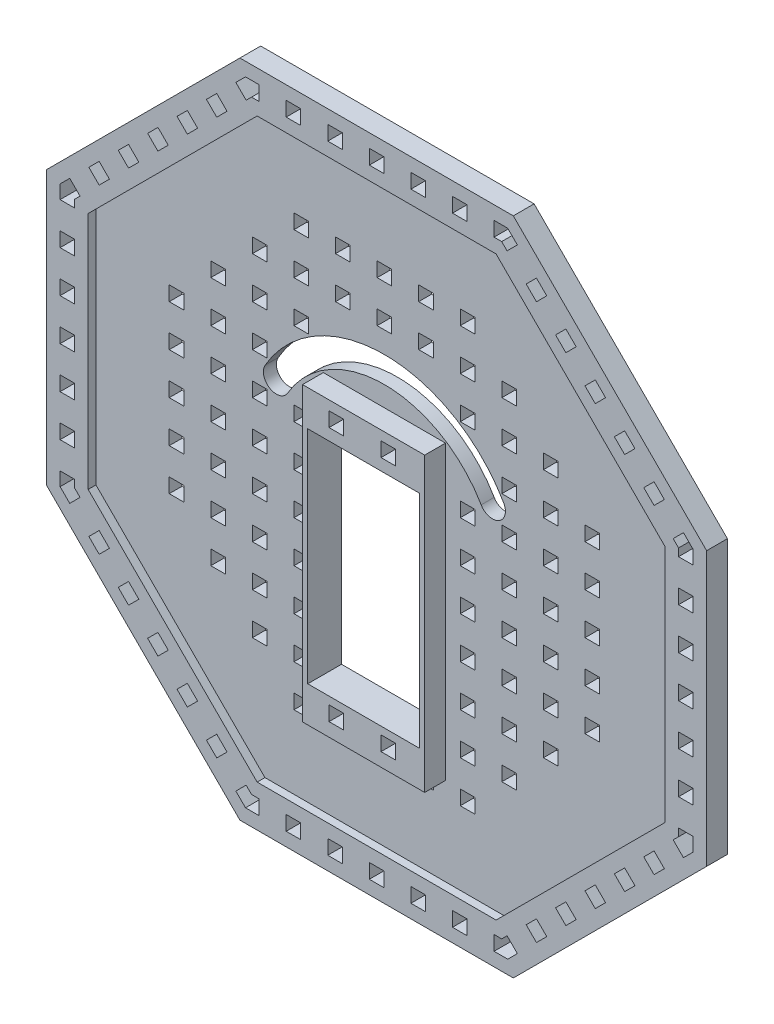
SolidWorks part; units mm, degrees
ref_plane "Plano frontal" through (0, 0, 0) normal (0, 0, 1) x (1, 0, 0)
ref_plane "Plano superior" through (0, 0, 0) normal (0, 1, 0) x (1, 0, 0)
ref_plane "Plano direito" through (0, 0, 0) normal (1, 0, 0) x (0, 0, -1)
sketch "Esboço1" plane through (0, 0, 0) normal (0, 0, 1) x (1, 0, 0)
  line L1 (63.5, -26.3026) -> (63.5, 26.3026)
  line L2 (63.5, 26.3026) -> (26.3026, 63.5)
  line L3 (26.3026, 63.5) -> (-26.3026, 63.5)
  line L4 (-26.3026, 63.5) -> (-63.5, 26.3026)
  line L5 (-63.5, 26.3026) -> (-63.5, -26.3026)
  line L6 (-63.5, -26.3026) -> (-26.3026, -63.5)
  line L7 (-26.3026, -63.5) -> (26.3026, -63.5)
  line L8 (26.3026, -63.5) -> (63.5, -26.3026)
  circle A0 centre (0, 0) radius 63.5 construction
  dimension "D1" = 127
extrude "Ressalto-extrusão1" add sketch "Esboço1" along normal blind 2.5
sketch "Esboço3"
sketch "Esboço2" plane through (0, 0, 0) normal (0, 0, -1) x (-1, 0, 0)
  line L0 (-45, 0) -> (45, 0) construction
  line L1 (-28.75, 0) -> (28.75, 0) construction
  line L2 (28.75, 0) -> (28.75, 8.5) construction
  line L3 (0, 0) -> (0, 75.734) construction
  line L4 (54, 24) -> (36, 24)
  line L5 (57, 21) -> (57, -21)
  line L6 (54, -24) -> (36, -24)
  line L7 (33, 21) -> (33, -21)
  line L8 (57, 24) -> (33, -24) construction
  line L9 (57, -24) -> (33, 24) construction
  line L10 (-57, -24) -> (-33, 24) construction
  line L11 (-57, 24) -> (-33, -24) construction
  line L12 (-28.75, 0) -> (-28.75, 8.5) construction
  line L13 (-33, 21) -> (-33, -21)
  line L14 (-54, -24) -> (-36, -24)
  line L15 (-57, 21) -> (-57, -21)
  line L16 (-54, 24) -> (-36, 24)
  line L17 (0, 0) -> (0, -57) construction
  line L18 (0, -57) -> (-6.731, -57) construction
  circle A0 centre (28.75, 8.5) radius 1.15
  circle A1 centre (28.75, -8.5) radius 1.15
  arc A2 (36, 24) -> (33, 21) centre (36, 21) ccw
  arc A3 (36, -24) -> (33, -21) centre (36, -21) cw
  arc A4 (57, -21) -> (54, -24) centre (54, -21) cw
  arc A5 (54, 24) -> (57, 21) centre (54, 21) cw
  arc A6 (-54, 24) -> (-57, 21) centre (-54, 21) ccw
  arc A7 (-57, -21) -> (-54, -24) centre (-54, -21) ccw
  arc A8 (-36, -24) -> (-33, -21) centre (-36, -21) ccw
  arc A9 (-36, 24) -> (-33, 21) centre (-36, 21) cw
  circle A10 centre (-28.75, -8.5) radius 1.15
  circle A11 centre (-28.75, 8.5) radius 1.15
  circle A12 centre (-6.731, -57) radius 1.15
  circle A13 centre (6.731, -57) radius 1.15
  circle A14 centre (6.731, 57) radius 1.15
  circle A15 centre (-6.731, 57) radius 1.15
  dimension "D6" = 3
  dimension "D8" = 6.731
  dimension "D1" = 45
  dimension "D2" = 48
  dimension "D3" = 24
  dimension "D4" = 28.75
  dimension "D5" = 8.5
  dimension "D7" = 57
sketch "Esboço4" plane through (0, 0, 0) normal (0, 0, -1) x (-1, 0, 0)
  line L0 (-9.75, 9.75) -> (-9.75, -30.75) construction
  line L1 (-9.75, -30.75) -> (9.75, -30.75) construction
  line L2 (9.75, -30.75) -> (9.75, 9.75) construction
  line L3 (9.75, 9.75) -> (-9.75, 9.75) construction
  line L4 (-10.75, 10.75) -> (-10.75, -31.75)
  line L5 (-4.5, -34.6089) -> (5, -34.6089) construction
  line L6 (10.75, -31.75) -> (10.75, 10.75)
  line L7 (10.75, 10.75) -> (-10.75, 10.75)
  line L8 (5, -34.6089) -> (5, 14.3911) construction
  line L9 (5, 14.3911) -> (-4.5, 14.3911) construction
  line L11 (-4.5, 14.3911) -> (-4.5, -34.6089) construction
  line L12 (0, 0) -> (-4.75, 0) construction
  line L13 (-4.75, 0) -> (5, 0) construction
  line L14 (5.25, 0) -> (5.25, 14.3911) construction
  line L15 (5.25, 14.3911) -> (5.25, -34.6089) construction
  line L16 (-3.35, -36.0089) -> (-6.15, -33.2089) construction
  line L23 (-6.15, -33.2089) -> (-3.35, -33.2089)
  line L24 (-6.15, -36.0089) -> (-3.35, -36.0089)
  line L25 (-6.15, -36.0089) -> (-3.35, -33.2089) construction
  line L26 (-6.15, -36.0089) -> (-6.15, -33.2089)
  line L27 (-3.35, -36.0089) -> (-3.35, -33.2089)
  line L28 (6.65, -36.0089) -> (3.85, -33.2089) construction
  line L29 (3.85, -33.2089) -> (6.65, -33.2089)
  line L30 (3.85, -36.0089) -> (6.65, -36.0089)
  line L31 (3.85, -36.0089) -> (6.65, -33.2089) construction
  line L32 (3.85, -36.0089) -> (3.85, -33.2089)
  line L33 (6.65, -36.0089) -> (6.65, -33.2089)
  line L34 (6.65, 12.9911) -> (3.85, 15.7911) construction
  line L35 (3.85, 15.7911) -> (6.65, 15.7911)
  line L36 (3.85, 12.9911) -> (6.65, 12.9911)
  line L37 (3.85, 12.9911) -> (6.65, 15.7911) construction
  line L38 (3.85, 12.9911) -> (3.85, 15.7911)
  line L39 (6.65, 12.9911) -> (6.65, 15.7911)
  line L40 (-3.35, 12.9911) -> (-6.15, 15.7911) construction
  line L41 (-6.15, 15.7911) -> (-3.35, 15.7911)
  line L42 (-6.15, 12.9911) -> (-3.35, 12.9911)
  line L43 (-6.15, 12.9911) -> (-3.35, 15.7911) construction
  line L44 (-6.15, 12.9911) -> (-6.15, 15.7911)
  line L45 (-3.35, 12.9911) -> (-3.35, 15.7911)
  line L46 (-10.75, -31.75) -> (10.75, -31.75)
  circle A0 centre (0, 0) radius 3 construction
  point P2 (9.75, -10.5)
  point P5 (10.75, -10.5)
  point P6 (0, 10.75)
  point P26 (-4.75, -34.6089)
  point P31 (5.25, -34.6089)
  point P41 (5.25, 14.3911)
  point P46 (-4.75, 14.3911)
  dimension "D2" = 2.8
  dimension "D3" = 2.8
  dimension "D4" = 2.8
  dimension "D5" = 2.8
extrude "Corte-extrusão1" cut sketch "Esboço4" against normal blind 5
sketch "Esboço5" plane through (0, 0, 0) normal (0, 0, 1) x (1, 0, 0)
  line L0 (-44.9013, -44.9013) -> (-42.0729, -42.0729) construction
  line L1 (-47.7297, -34.4361) -> (-49.7096, -36.416)
  line L2 (-42.0729, -40.093) -> (-44.0528, -42.0729)
  line L3 (-42.0729, -40.093) -> (-40.093, -42.0729)
  line L4 (-40.093, -42.0729) -> (-42.0729, -44.0528)
  line L5 (-44.0528, -42.0729) -> (-42.0729, -44.0528)
  line L6 (-42.0729, -40.093) -> (-42.0729, -44.0528) construction
  line L7 (-40.093, -42.0729) -> (-44.0528, -42.0729) construction
  line L8 (-47.7297, -34.4361) -> (-45.7498, -36.416)
  line L9 (-45.7498, -36.416) -> (-47.7297, -38.3959)
  line L10 (-49.7096, -36.416) -> (-47.7297, -38.3959)
  line L11 (-47.7297, -34.4361) -> (-47.7297, -38.3959) construction
  line L12 (-45.7498, -36.416) -> (-49.7096, -36.416) construction
  line L13 (-53.3866, -28.7792) -> (-55.3665, -30.7591)
  line L14 (-53.3866, -28.7792) -> (-51.4067, -30.7591)
  line L15 (-51.4067, -30.7591) -> (-53.3866, -32.739)
  line L16 (-55.3665, -30.7591) -> (-53.3866, -32.739)
  line L17 (-53.3866, -28.7792) -> (-53.3866, -32.739) construction
  line L18 (-51.4067, -30.7591) -> (-55.3665, -30.7591) construction
  line L19 (-60.9, 25.2256) -> (-59.0434, 27.0822)
  line L20 (-57.0635, 25.1023) -> (-59.0434, 27.0822)
  line L21 (-58.1, 6.6) -> (-58.1, 9.4)
  line L22 (-58.1, -1.4) -> (-58.1, 1.4)
  line L23 (-58.1, -1.4) -> (-60.9, -1.4)
  line L24 (-60.9, -1.4) -> (-60.9, 1.4)
  line L25 (-58.1, 1.4) -> (-60.9, 1.4)
  line L26 (-30.7591, -51.4067) -> (-30.7591, -55.3665) construction
  line L27 (-28.7792, -53.3866) -> (-32.739, -53.3866) construction
  line L28 (-36.416, -45.7498) -> (-36.416, -49.7096) construction
  line L29 (-34.4361, -47.7297) -> (-38.3959, -47.7297) construction
  line L30 (-42.0729, -40.093) -> (-42.0729, -44.0528) construction
  line L31 (-40.093, -42.0729) -> (-44.0528, -42.0729) construction
  line L32 (-25.2256, -60.9) -> (-27.0822, -59.0434)
  line L33 (-25.1023, -57.0635) -> (-27.0822, -59.0434)
  line L34 (-58.1, 6.6) -> (-60.9, 6.6)
  line L35 (-30.7591, -55.3665) -> (-32.739, -53.3866)
  line L36 (-30.7591, -51.4067) -> (-32.739, -53.3866)
  line L37 (-28.7792, -53.3866) -> (-30.7591, -51.4067)
  line L38 (-28.7792, -53.3866) -> (-30.7591, -55.3665)
  line L39 (-36.416, -49.7096) -> (-38.3959, -47.7297)
  line L40 (-36.416, -45.7498) -> (-38.3959, -47.7297)
  line L41 (-34.4361, -47.7297) -> (-36.416, -45.7498)
  line L42 (-34.4361, -47.7297) -> (-36.416, -49.7096)
  line L43 (0, -63.5) -> (0, -59.5) construction
  line L44 (-6.6, -58.1) -> (-9.4, -58.1)
  line L45 (1.4, -58.1) -> (-1.4, -58.1)
  line L46 (1.4, -58.1) -> (1.4, -60.9)
  line L47 (1.4, -60.9) -> (-1.4, -60.9)
  line L48 (-1.4, -58.1) -> (-1.4, -60.9)
  line L49 (1.4, -58.1) -> (-1.4, -60.9) construction
  line L50 (1.4, -60.9) -> (-1.4, -58.1) construction
  line L51 (-6.6, -58.1) -> (-6.6, -60.9)
  line L52 (-6.6, -60.9) -> (-9.4, -60.9)
  line L53 (-9.4, -58.1) -> (-9.4, -60.9)
  line L54 (-6.6, -58.1) -> (-9.4, -60.9) construction
  line L55 (-6.6, -60.9) -> (-9.4, -58.1) construction
  line L56 (-14.6, -58.1) -> (-17.4, -58.1)
  line L57 (-14.6, -58.1) -> (-14.6, -60.9)
  line L58 (-14.6, -60.9) -> (-17.4, -60.9)
  line L59 (-17.4, -58.1) -> (-17.4, -60.9)
  line L60 (-14.6, -58.1) -> (-17.4, -60.9) construction
  line L61 (-14.6, -60.9) -> (-17.4, -58.1) construction
  line L62 (-22.6, -58.1) -> (-24.0658, -58.1)
  line L63 (-22.6, -58.1) -> (-22.6, -60.9)
  line L64 (-22.6, -60.9) -> (-25.2256, -60.9)
  line L65 (-60.9, 6.6) -> (-60.9, 9.4)
  line L66 (-58.1, 9.4) -> (-60.9, 9.4)
  line L67 (-58.1, 14.6) -> (-58.1, 17.4)
  line L68 (-58.1, 14.6) -> (-60.9, 14.6)
  line L69 (-60.9, 14.6) -> (-60.9, 17.4)
  line L70 (-58.1, 17.4) -> (-60.9, 17.4)
  line L71 (-17.4, 6.6) -> (-14.6, 6.6)
  line L72 (16, 24) -> (0, 24) construction
  line L73 (0, 24) -> (-16, 24) construction
  line L74 (-24.0658, -58.1) -> (-25.1023, -57.0635)
  line L75 (-58.1, 22.6) -> (-58.1, 24.0658)
  line L76 (-58.1, 22.6) -> (-60.9, 22.6)
  line L77 (-25.4, 46.6) -> (-22.6, 49.4) construction
  line L78 (-60.9, 22.6) -> (-60.9, 25.2256)
  line L79 (-58.1, 24.0658) -> (-57.0635, 25.1023)
  line L80 (-58.1, -24.0658) -> (-57.0635, -25.1023)
  line L81 (-60.9, -22.6) -> (-60.9, -25.2256)
  line L82 (-58.1, -22.6) -> (-60.9, -22.6)
  line L83 (-58.1, -22.6) -> (-58.1, -24.0658)
  line L84 (-58.1, -17.4) -> (-60.9, -17.4)
  line L85 (-60.9, -14.6) -> (-60.9, -17.4)
  line L86 (-58.1, -14.6) -> (-60.9, -14.6)
  line L87 (-58.1, -14.6) -> (-58.1, -17.4)
  line L88 (-58.1, -9.4) -> (-60.9, -9.4)
  line L89 (-60.9, -6.6) -> (-60.9, -9.4)
  line L90 (-58.1, -6.6) -> (-60.9, -6.6)
  line L91 (-58.1, -6.6) -> (-58.1, -9.4)
  line L92 (0, 0) -> (0, 63.5) construction
  line L93 (-25.4, 49.4) -> (-22.6, 46.6) construction
  line L94 (-57.0635, -25.1023) -> (-59.0434, -27.0822)
  line L95 (-60.9, -25.2256) -> (-59.0434, -27.0822)
  line L96 (-63.5, 0) -> (-59.5, 0) construction
  line L97 (-58.1, -1.4) -> (-60.9, 1.4) construction
  line L98 (-60.9, -1.4) -> (-58.1, 1.4) construction
  line L99 (14.6, -60.9) -> (17.4, -58.1) construction
  line L100 (14.6, -58.1) -> (17.4, -60.9) construction
  line L101 (6.6, -60.9) -> (9.4, -58.1) construction
  line L102 (6.6, -58.1) -> (9.4, -60.9) construction
  line L103 (40.093, -42.0729) -> (44.0528, -42.0729) construction
  line L104 (42.0729, -40.093) -> (42.0729, -44.0528) construction
  line L105 (34.4361, -47.7297) -> (38.3959, -47.7297) construction
  line L106 (36.416, -45.7498) -> (36.416, -49.7096) construction
  line L107 (28.7792, -53.3866) -> (32.739, -53.3866) construction
  line L108 (30.7591, -51.4067) -> (30.7591, -55.3665) construction
  line L109 (-58.1, 6.6) -> (-60.9, 9.4) construction
  line L110 (-60.9, 6.6) -> (-58.1, 9.4) construction
  line L111 (-58.1, 14.6) -> (-60.9, 17.4) construction
  line L112 (51.4067, -30.7591) -> (55.3665, -30.7591) construction
  line L113 (53.3866, -28.7792) -> (53.3866, -32.739) construction
  line L114 (45.7498, -36.416) -> (49.7096, -36.416) construction
  line L115 (47.7297, -34.4361) -> (47.7297, -38.3959) construction
  line L116 (40.093, -42.0729) -> (44.0528, -42.0729) construction
  line L117 (42.0729, -40.093) -> (42.0729, -44.0528) construction
  line L118 (44.9013, -44.9013) -> (42.0729, -42.0729) construction
  line L119 (-60.9, 14.6) -> (-58.1, 17.4) construction
  line L120 (-60.9, -14.6) -> (-58.1, -17.4) construction
  line L121 (-58.1, -14.6) -> (-60.9, -17.4) construction
  line L122 (-60.9, -6.6) -> (-58.1, -9.4) construction
  line L123 (-58.1, -6.6) -> (-60.9, -9.4) construction
  line L124 (25.2256, 60.9) -> (27.0822, 59.0434)
  line L125 (25.1023, 57.0635) -> (27.0822, 59.0434)
  line L126 (24.0658, -58.1) -> (25.1023, -57.0635)
  line L127 (6.6, 58.1) -> (9.4, 58.1)
  line L128 (-1.4, 58.1) -> (1.4, 58.1)
  line L129 (-1.4, 58.1) -> (-1.4, 60.9)
  line L130 (-1.4, 60.9) -> (1.4, 60.9)
  line L131 (22.6, -60.9) -> (25.2256, -60.9)
  line L132 (22.6, -58.1) -> (22.6, -60.9)
  line L133 (22.6, -58.1) -> (24.0658, -58.1)
  line L134 (17.4, -58.1) -> (17.4, -60.9)
  line L135 (14.6, -60.9) -> (17.4, -60.9)
  line L136 (14.6, -58.1) -> (14.6, -60.9)
  line L137 (14.6, -58.1) -> (17.4, -58.1)
  line L138 (9.4, -58.1) -> (9.4, -60.9)
  line L139 (6.6, -60.9) -> (9.4, -60.9)
  line L140 (6.6, -58.1) -> (6.6, -60.9)
  line L141 (6.6, -58.1) -> (9.4, -58.1)
  line L142 (34.4361, -47.7297) -> (36.416, -49.7096)
  line L143 (40.093, -42.0729) -> (42.0729, -44.0528)
  line L144 (42.0729, -40.093) -> (44.0528, -42.0729)
  line L145 (34.4361, -47.7297) -> (36.416, -45.7498)
  line L146 (36.416, -45.7498) -> (38.3959, -47.7297)
  line L147 (36.416, -49.7096) -> (38.3959, -47.7297)
  line L148 (28.7792, -53.3866) -> (30.7591, -55.3665)
  line L149 (28.7792, -53.3866) -> (30.7591, -51.4067)
  line L150 (30.7591, -51.4067) -> (32.739, -53.3866)
  line L151 (30.7591, -55.3665) -> (32.739, -53.3866)
  line L152 (1.4, 58.1) -> (1.4, 60.9)
  line L153 (25.1023, -57.0635) -> (27.0822, -59.0434)
  line L154 (25.2256, -60.9) -> (27.0822, -59.0434)
  line L155 (6.6, 58.1) -> (6.6, 60.9)
  line L156 (6.6, 60.9) -> (9.4, 60.9)
  line L157 (9.4, 58.1) -> (9.4, 60.9)
  line L158 (14.6, 58.1) -> (17.4, 58.1)
  line L159 (55.3665, -30.7591) -> (53.3866, -32.739)
  line L160 (51.4067, -30.7591) -> (53.3866, -32.739)
  line L161 (53.3866, -28.7792) -> (51.4067, -30.7591)
  line L162 (53.3866, -28.7792) -> (55.3665, -30.7591)
  line L163 (49.7096, -36.416) -> (47.7297, -38.3959)
  line L164 (45.7498, -36.416) -> (47.7297, -38.3959)
  line L165 (47.7297, -34.4361) -> (45.7498, -36.416)
  line L166 (44.0528, -42.0729) -> (42.0729, -44.0528)
  line L167 (42.0729, -40.093) -> (40.093, -42.0729)
  line L168 (47.7297, -34.4361) -> (49.7096, -36.416)
  line L169 (44.9013, 44.9013) -> (42.0729, 42.0729) construction
  line L170 (42.0729, 40.093) -> (42.0729, 44.0528) construction
  line L171 (40.093, 42.0729) -> (44.0528, 42.0729) construction
  line L172 (47.7297, 34.4361) -> (47.7297, 38.3959) construction
  line L173 (45.7498, 36.416) -> (49.7096, 36.416) construction
  line L174 (53.3866, 28.7792) -> (53.3866, 32.739) construction
  line L175 (51.4067, 30.7591) -> (55.3665, 30.7591) construction
  line L176 (14.6, 58.1) -> (14.6, 60.9)
  line L177 (14.6, 60.9) -> (17.4, 60.9)
  line L178 (30.7591, 51.4067) -> (30.7591, 55.3665) construction
  line L179 (28.7792, 53.3866) -> (32.739, 53.3866) construction
  line L180 (36.416, 45.7498) -> (36.416, 49.7096) construction
  line L181 (34.4361, 47.7297) -> (38.3959, 47.7297) construction
  line L182 (42.0729, 40.093) -> (42.0729, 44.0528) construction
  line L183 (40.093, 42.0729) -> (44.0528, 42.0729) construction
  line L184 (17.4, 58.1) -> (17.4, 60.9)
  line L185 (22.6, 58.1) -> (24.0658, 58.1)
  line L186 (22.6, 58.1) -> (22.6, 60.9)
  line L187 (22.6, 60.9) -> (25.2256, 60.9)
  line L188 (24.0658, 58.1) -> (25.1023, 57.0635)
  line L189 (-24.0658, 58.1) -> (-25.1023, 57.0635)
  line L190 (-22.6, 60.9) -> (-25.2256, 60.9)
  line L191 (-22.6, 58.1) -> (-22.6, 60.9)
  line L192 (-22.6, 58.1) -> (-24.0658, 58.1)
  line L193 (-17.4, 58.1) -> (-17.4, 60.9)
  line L194 (-14.6, 60.9) -> (-17.4, 60.9)
  line L195 (-14.6, 58.1) -> (-14.6, 60.9)
  line L196 (-14.6, 58.1) -> (-17.4, 58.1)
  line L197 (-9.4, 58.1) -> (-9.4, 60.9)
  line L198 (-6.6, 60.9) -> (-9.4, 60.9)
  line L199 (-6.6, 58.1) -> (-6.6, 60.9)
  line L200 (-6.6, 58.1) -> (-9.4, 58.1)
  line L201 (-25.1023, 57.0635) -> (-27.0822, 59.0434)
  line L202 (-25.2256, 60.9) -> (-27.0822, 59.0434)
  line L203 (-40.093, 42.0729) -> (-44.0528, 42.0729) construction
  line L204 (-42.0729, 40.093) -> (-42.0729, 44.0528) construction
  line L205 (-34.4361, 47.7297) -> (-38.3959, 47.7297) construction
  line L206 (-36.416, 45.7498) -> (-36.416, 49.7096) construction
  line L207 (-28.7792, 53.3866) -> (-32.739, 53.3866) construction
  line L208 (-30.7591, 51.4067) -> (-30.7591, 55.3665) construction
  line L209 (0, 63.5) -> (0, 59.5) construction
  line L210 (-1.4, 58.1) -> (1.4, 60.9) construction
  line L211 (-51.4067, 30.7591) -> (-55.3665, 30.7591) construction
  line L212 (-53.3866, 28.7792) -> (-53.3866, 32.739) construction
  line L213 (-45.7498, 36.416) -> (-49.7096, 36.416) construction
  line L214 (-47.7297, 34.4361) -> (-47.7297, 38.3959) construction
  line L215 (-40.093, 42.0729) -> (-44.0528, 42.0729) construction
  line L216 (-42.0729, 40.093) -> (-42.0729, 44.0528) construction
  line L217 (-44.9013, 44.9013) -> (-42.0729, 42.0729) construction
  line L218 (47.7297, 34.4361) -> (49.7096, 36.416)
  line L219 (42.0729, 40.093) -> (44.0528, 42.0729)
  line L220 (42.0729, 40.093) -> (40.093, 42.0729)
  line L221 (40.093, 42.0729) -> (42.0729, 44.0528)
  line L222 (44.0528, 42.0729) -> (42.0729, 44.0528)
  line L223 (47.7297, 34.4361) -> (45.7498, 36.416)
  line L224 (45.7498, 36.416) -> (47.7297, 38.3959)
  line L225 (49.7096, 36.416) -> (47.7297, 38.3959)
  line L226 (53.3866, 28.7792) -> (55.3665, 30.7591)
  line L227 (53.3866, 28.7792) -> (51.4067, 30.7591)
  line L228 (51.4067, 30.7591) -> (53.3866, 32.739)
  line L229 (55.3665, 30.7591) -> (53.3866, 32.739)
  line L230 (-1.4, 60.9) -> (1.4, 58.1) construction
  line L231 (6.6, 58.1) -> (9.4, 60.9) construction
  line L232 (6.6, 60.9) -> (9.4, 58.1) construction
  line L233 (14.6, 58.1) -> (17.4, 60.9) construction
  line L234 (14.6, 60.9) -> (17.4, 58.1) construction
  line L235 (-14.6, 60.9) -> (-17.4, 58.1) construction
  line L236 (-14.6, 58.1) -> (-17.4, 60.9) construction
  line L237 (30.7591, 55.3665) -> (32.739, 53.3866)
  line L238 (30.7591, 51.4067) -> (32.739, 53.3866)
  line L239 (28.7792, 53.3866) -> (30.7591, 51.4067)
  line L240 (28.7792, 53.3866) -> (30.7591, 55.3665)
  line L241 (36.416, 49.7096) -> (38.3959, 47.7297)
  line L242 (36.416, 45.7498) -> (38.3959, 47.7297)
  line L243 (34.4361, 47.7297) -> (36.416, 45.7498)
  line L244 (34.4361, 47.7297) -> (36.416, 49.7096)
  line L245 (-6.6, 60.9) -> (-9.4, 58.1) construction
  line L246 (-6.6, 58.1) -> (-9.4, 60.9) construction
  line L247 (60.9, -25.2256) -> (59.0434, -27.0822)
  line L248 (57.0635, -25.1023) -> (59.0434, -27.0822)
  line L249 (58.1, -6.6) -> (58.1, -9.4)
  line L250 (58.1, 1.4) -> (58.1, -1.4)
  line L251 (58.1, 1.4) -> (60.9, 1.4)
  line L252 (60.9, 1.4) -> (60.9, -1.4)
  line L253 (58.1, -1.4) -> (60.9, -1.4)
  line L254 (58.1, -6.6) -> (60.9, -6.6)
  line L255 (60.9, -6.6) -> (60.9, -9.4)
  line L256 (58.1, -9.4) -> (60.9, -9.4)
  line L257 (58.1, -14.6) -> (58.1, -17.4)
  line L258 (58.1, -14.6) -> (60.9, -14.6)
  line L259 (60.9, -14.6) -> (60.9, -17.4)
  line L260 (58.1, -17.4) -> (60.9, -17.4)
  line L261 (58.1, -22.6) -> (58.1, -24.0658)
  line L262 (58.1, -22.6) -> (60.9, -22.6)
  line L263 (60.9, -22.6) -> (60.9, -25.2256)
  line L264 (58.1, -24.0658) -> (57.0635, -25.1023)
  line L265 (58.1, 24.0658) -> (57.0635, 25.1023)
  line L266 (60.9, 22.6) -> (60.9, 25.2256)
  line L267 (58.1, 22.6) -> (60.9, 22.6)
  line L268 (58.1, 22.6) -> (58.1, 24.0658)
  line L269 (58.1, 17.4) -> (60.9, 17.4)
  line L270 (60.9, 14.6) -> (60.9, 17.4)
  line L271 (58.1, 14.6) -> (60.9, 14.6)
  line L272 (58.1, 14.6) -> (58.1, 17.4)
  line L273 (58.1, 9.4) -> (60.9, 9.4)
  line L274 (60.9, 6.6) -> (60.9, 9.4)
  line L275 (58.1, 6.6) -> (60.9, 6.6)
  line L276 (58.1, 6.6) -> (58.1, 9.4)
  line L277 (57.0635, 25.1023) -> (59.0434, 27.0822)
  line L278 (60.9, 25.2256) -> (59.0434, 27.0822)
  line L279 (63.5, 0) -> (59.5, 0) construction
  line L280 (58.1, 1.4) -> (60.9, -1.4) construction
  line L281 (60.9, 1.4) -> (58.1, -1.4) construction
  line L282 (58.1, -6.6) -> (60.9, -9.4) construction
  line L283 (60.9, -6.6) -> (58.1, -9.4) construction
  line L284 (58.1, -14.6) -> (60.9, -17.4) construction
  line L285 (60.9, -14.6) -> (58.1, -17.4) construction
  line L286 (60.9, 14.6) -> (58.1, 17.4) construction
  line L287 (-34.4361, 47.7297) -> (-36.416, 49.7096)
  line L288 (-40.093, 42.0729) -> (-42.0729, 44.0528)
  line L289 (-42.0729, 40.093) -> (-44.0528, 42.0729)
  line L290 (-34.4361, 47.7297) -> (-36.416, 45.7498)
  line L291 (-36.416, 45.7498) -> (-38.3959, 47.7297)
  line L292 (-36.416, 49.7096) -> (-38.3959, 47.7297)
  line L293 (-28.7792, 53.3866) -> (-30.7591, 55.3665)
  line L294 (-28.7792, 53.3866) -> (-30.7591, 51.4067)
  line L295 (-30.7591, 51.4067) -> (-32.739, 53.3866)
  line L296 (-30.7591, 55.3665) -> (-32.739, 53.3866)
  line L297 (58.1, 14.6) -> (60.9, 17.4) construction
  line L298 (60.9, 6.6) -> (58.1, 9.4) construction
  line L299 (58.1, 6.6) -> (60.9, 9.4) construction
  line L304 (-55.3665, 30.7591) -> (-53.3866, 32.739)
  line L305 (-51.4067, 30.7591) -> (-53.3866, 32.739)
  line L306 (-53.3866, 28.7792) -> (-51.4067, 30.7591)
  line L307 (-53.3866, 28.7792) -> (-55.3665, 30.7591)
  line L308 (-49.7096, 36.416) -> (-47.7297, 38.3959)
  line L309 (-45.7498, 36.416) -> (-47.7297, 38.3959)
  line L310 (-47.7297, 34.4361) -> (-45.7498, 36.416)
  line L311 (-44.0528, 42.0729) -> (-42.0729, 44.0528)
  line L312 (-42.0729, 40.093) -> (-40.093, 42.0729)
  line L313 (-47.7297, 34.4361) -> (-49.7096, 36.416)
  line L314 (-17.4, 46.6) -> (-14.6, 49.4) construction
  line L315 (-14.6, 9.4) -> (-14.6, 6.6)
  line L316 (-17.4, 9.4) -> (-14.6, 9.4)
  line L317 (-17.4, 9.4) -> (-17.4, 6.6)
  line L318 (-17.4, 6.6) -> (-14.6, 9.4) construction
  line L319 (-17.4, 9.4) -> (-14.6, 6.6) construction
  line L320 (-17.4, -1.4) -> (-14.6, -1.4)
  line L321 (-14.6, 1.4) -> (-14.6, -1.4)
  line L322 (-17.4, 1.4) -> (-14.6, 1.4)
  line L323 (-17.4, 1.4) -> (-17.4, -1.4)
  line L324 (-17.4, -1.4) -> (-14.6, 1.4) construction
  line L325 (-17.4, 1.4) -> (-14.6, -1.4) construction
  line L326 (17.4, 1.4) -> (14.6, -1.4) construction
  line L327 (17.4, -1.4) -> (14.6, 1.4) construction
  line L328 (17.4, 1.4) -> (17.4, -1.4)
  line L329 (17.4, 1.4) -> (14.6, 1.4)
  line L330 (14.6, 1.4) -> (14.6, -1.4)
  line L331 (17.4, -1.4) -> (14.6, -1.4)
  line L332 (25.4, 1.4) -> (22.6, -1.4) construction
  line L333 (25.4, -1.4) -> (22.6, 1.4) construction
  line L334 (25.4, 1.4) -> (25.4, -1.4)
  line L335 (25.4, 1.4) -> (22.6, 1.4)
  line L336 (22.6, 1.4) -> (22.6, -1.4)
  line L337 (25.4, -1.4) -> (22.6, -1.4)
  line L346 (0, 0) -> (76.7252, 0) construction
  line L347 (-17.4, -9.4) -> (-14.6, -9.4)
  line L348 (-14.6, -6.6) -> (-14.6, -9.4)
  line L349 (-17.4, -6.6) -> (-14.6, -6.6)
  line L350 (-17.4, -6.6) -> (-17.4, -9.4)
  line L351 (-17.4, -9.4) -> (-14.6, -6.6) construction
  line L352 (-17.4, -6.6) -> (-14.6, -9.4) construction
  line L362 (17.4, 9.4) -> (14.6, 6.6) construction
  line L363 (17.4, 6.6) -> (14.6, 9.4) construction
  line L364 (17.4, 9.4) -> (17.4, 6.6)
  line L365 (17.4, 9.4) -> (14.6, 9.4)
  line L366 (14.6, 9.4) -> (14.6, 6.6)
  line L367 (17.4, 6.6) -> (14.6, 6.6)
  line L368 (25.4, 9.4) -> (22.6, 6.6) construction
  line L369 (25.4, 6.6) -> (22.6, 9.4) construction
  line L370 (25.4, 9.4) -> (25.4, 6.6)
  line L371 (25.4, 9.4) -> (22.6, 9.4)
  line L372 (22.6, 9.4) -> (22.6, 6.6)
  line L373 (25.4, 6.6) -> (22.6, 6.6)
  line L404 (25.4, 17.4) -> (22.6, 14.6) construction
  line L405 (25.4, 14.6) -> (22.6, 17.4) construction
  line L406 (25.4, 17.4) -> (25.4, 14.6)
  line L407 (25.4, 17.4) -> (22.6, 17.4)
  line L408 (22.6, 17.4) -> (22.6, 14.6)
  line L409 (25.4, 14.6) -> (22.6, 14.6)
  line L434 (17.4, 25.4) -> (14.6, 22.6) construction
  line L435 (17.4, 22.6) -> (14.6, 25.4) construction
  line L436 (17.4, 25.4) -> (17.4, 22.6)
  line L437 (17.4, 25.4) -> (14.6, 25.4)
  line L438 (14.6, 25.4) -> (14.6, 22.6)
  line L439 (17.4, 22.6) -> (14.6, 22.6)
  line L440 (25.4, 25.4) -> (22.6, 22.6) construction
  line L441 (25.4, 22.6) -> (22.6, 25.4) construction
  line L442 (25.4, 25.4) -> (25.4, 22.6)
  line L443 (25.4, 25.4) -> (22.6, 25.4)
  line L444 (22.6, 25.4) -> (22.6, 22.6)
  line L445 (25.4, 22.6) -> (22.6, 22.6)
  line L464 (9.4, 33.4) -> (6.6, 30.6) construction
  line L465 (9.4, 30.6) -> (6.6, 33.4) construction
  line L466 (9.4, 33.4) -> (9.4, 30.6)
  line L467 (9.4, 33.4) -> (6.6, 33.4)
  line L468 (6.6, 33.4) -> (6.6, 30.6)
  line L469 (9.4, 30.6) -> (6.6, 30.6)
  line L470 (17.4, 33.4) -> (14.6, 30.6) construction
  line L471 (17.4, 30.6) -> (14.6, 33.4) construction
  line L472 (17.4, 33.4) -> (17.4, 30.6)
  line L473 (17.4, 33.4) -> (14.6, 33.4)
  line L474 (14.6, 33.4) -> (14.6, 30.6)
  line L475 (17.4, 30.6) -> (14.6, 30.6)
  line L476 (25.4, 33.4) -> (22.6, 30.6) construction
  line L477 (25.4, 30.6) -> (22.6, 33.4) construction
  line L478 (25.4, 33.4) -> (25.4, 30.6)
  line L479 (25.4, 33.4) -> (22.6, 33.4)
  line L480 (22.6, 33.4) -> (22.6, 30.6)
  line L481 (25.4, 30.6) -> (22.6, 30.6)
  line L482 (33.4, 33.4) -> (30.6, 30.6) construction
  line L483 (33.4, 30.6) -> (30.6, 33.4) construction
  line L484 (33.4, 33.4) -> (33.4, 30.6)
  line L485 (33.4, 33.4) -> (30.6, 33.4)
  line L486 (30.6, 33.4) -> (30.6, 30.6)
  line L487 (33.4, 30.6) -> (30.6, 30.6)
  line L488 (41.4, 33.4) -> (38.6, 30.6) construction
  line L489 (41.4, 30.6) -> (38.6, 33.4) construction
  line L490 (41.4, 33.4) -> (41.4, 30.6)
  line L491 (41.4, 33.4) -> (38.6, 33.4)
  line L492 (38.6, 33.4) -> (38.6, 30.6)
  line L493 (41.4, 30.6) -> (38.6, 30.6)
  line L500 (9.4, 41.4) -> (6.6, 38.6) construction
  line L501 (9.4, 38.6) -> (6.6, 41.4) construction
  line L502 (9.4, 41.4) -> (9.4, 38.6)
  line L503 (9.4, 41.4) -> (6.6, 41.4)
  line L504 (6.6, 41.4) -> (6.6, 38.6)
  line L505 (9.4, 38.6) -> (6.6, 38.6)
  line L506 (17.4, 41.4) -> (14.6, 38.6) construction
  line L507 (17.4, 38.6) -> (14.6, 41.4) construction
  line L508 (17.4, 41.4) -> (17.4, 38.6)
  line L509 (17.4, 41.4) -> (14.6, 41.4)
  line L510 (14.6, 41.4) -> (14.6, 38.6)
  line L511 (17.4, 38.6) -> (14.6, 38.6)
  line L512 (25.4, 41.4) -> (22.6, 38.6) construction
  line L513 (25.4, 38.6) -> (22.6, 41.4) construction
  line L514 (25.4, 41.4) -> (25.4, 38.6)
  line L515 (25.4, 41.4) -> (22.6, 41.4)
  line L516 (22.6, 41.4) -> (22.6, 38.6)
  line L517 (25.4, 38.6) -> (22.6, 38.6)
  line L518 (33.4, 41.4) -> (30.6, 38.6) construction
  line L519 (33.4, 38.6) -> (30.6, 41.4) construction
  line L520 (33.4, 41.4) -> (33.4, 38.6)
  line L521 (33.4, 41.4) -> (30.6, 41.4)
  line L522 (30.6, 41.4) -> (30.6, 38.6)
  line L523 (33.4, 38.6) -> (30.6, 38.6)
  line L536 (9.4, 49.4) -> (6.6, 46.6) construction
  line L537 (9.4, 46.6) -> (6.6, 49.4) construction
  line L538 (9.4, 49.4) -> (9.4, 46.6)
  line L539 (9.4, 49.4) -> (6.6, 49.4)
  line L540 (6.6, 49.4) -> (6.6, 46.6)
  line L541 (9.4, 46.6) -> (6.6, 46.6)
  line L542 (17.4, 49.4) -> (14.6, 46.6) construction
  line L543 (17.4, 46.6) -> (14.6, 49.4) construction
  line L544 (17.4, 49.4) -> (17.4, 46.6)
  line L545 (17.4, 49.4) -> (14.6, 49.4)
  line L546 (14.6, 49.4) -> (14.6, 46.6)
  line L547 (17.4, 46.6) -> (14.6, 46.6)
  line L548 (25.4, 49.4) -> (22.6, 46.6) construction
  line L549 (25.4, 46.6) -> (22.6, 49.4) construction
  line L550 (25.4, 49.4) -> (25.4, 46.6)
  line L551 (25.4, 49.4) -> (22.6, 49.4)
  line L552 (22.6, 49.4) -> (22.6, 46.6)
  line L553 (25.4, 46.6) -> (22.6, 46.6)
  line L584 (1.4, 25.4) -> (-1.4, 22.6) construction
  line L585 (1.4, 22.6) -> (-1.4, 25.4) construction
  line L586 (1.4, 25.4) -> (1.4, 22.6)
  line L587 (1.4, 25.4) -> (-1.4, 25.4)
  line L588 (-1.4, 25.4) -> (-1.4, 22.6)
  line L589 (1.4, 22.6) -> (-1.4, 22.6)
  line L590 (1.4, 33.4) -> (-1.4, 30.6) construction
  line L591 (1.4, 30.6) -> (-1.4, 33.4) construction
  line L592 (1.4, 33.4) -> (1.4, 30.6)
  line L593 (1.4, 33.4) -> (-1.4, 33.4)
  line L594 (-1.4, 33.4) -> (-1.4, 30.6)
  line L595 (1.4, 30.6) -> (-1.4, 30.6)
  line L596 (1.4, 41.4) -> (-1.4, 38.6) construction
  line L597 (1.4, 38.6) -> (-1.4, 41.4) construction
  line L598 (1.4, 41.4) -> (1.4, 38.6)
  line L599 (1.4, 41.4) -> (-1.4, 41.4)
  line L600 (-1.4, 41.4) -> (-1.4, 38.6)
  line L601 (1.4, 38.6) -> (-1.4, 38.6)
  line L602 (1.4, 49.4) -> (-1.4, 46.6) construction
  line L603 (1.4, 46.6) -> (-1.4, 49.4) construction
  line L604 (1.4, 49.4) -> (1.4, 46.6)
  line L605 (1.4, 49.4) -> (-1.4, 49.4)
  line L606 (-1.4, 49.4) -> (-1.4, 46.6)
  line L607 (1.4, 46.6) -> (-1.4, 46.6)
  line L608 (-17.4, 49.4) -> (-14.6, 46.6) construction
  line L609 (-9.4, 46.6) -> (-6.6, 49.4) construction
  line L610 (-9.4, 49.4) -> (-6.6, 46.6) construction
  line L611 (-33.4, 38.6) -> (-30.6, 41.4) construction
  line L612 (-33.4, 41.4) -> (-30.6, 38.6) construction
  line L613 (-25.4, 38.6) -> (-22.6, 41.4) construction
  line L614 (-25.4, 41.4) -> (-22.6, 38.6) construction
  line L615 (-17.4, 38.6) -> (-14.6, 41.4) construction
  line L616 (-17.4, 41.4) -> (-14.6, 38.6) construction
  line L617 (-9.4, 38.6) -> (-6.6, 41.4) construction
  line L618 (-9.4, 41.4) -> (-6.6, 38.6) construction
  line L623 (-25.4, 46.6) -> (-22.6, 46.6)
  line L624 (-22.6, 49.4) -> (-22.6, 46.6)
  line L625 (-25.4, 49.4) -> (-22.6, 49.4)
  line L626 (-25.4, 49.4) -> (-25.4, 46.6)
  line L627 (-17.4, 46.6) -> (-14.6, 46.6)
  line L628 (-14.6, 49.4) -> (-14.6, 46.6)
  line L629 (-17.4, 49.4) -> (-14.6, 49.4)
  line L630 (-17.4, 49.4) -> (-17.4, 46.6)
  line L631 (-9.4, 46.6) -> (-6.6, 46.6)
  line L632 (-6.6, 49.4) -> (-6.6, 46.6)
  line L633 (-9.4, 49.4) -> (-6.6, 49.4)
  line L634 (-9.4, 49.4) -> (-9.4, 46.6)
  line L635 (-33.4, 38.6) -> (-30.6, 38.6)
  line L636 (-30.6, 41.4) -> (-30.6, 38.6)
  line L637 (-33.4, 41.4) -> (-30.6, 41.4)
  line L638 (-33.4, 41.4) -> (-33.4, 38.6)
  line L639 (-25.4, 38.6) -> (-22.6, 38.6)
  line L640 (-22.6, 41.4) -> (-22.6, 38.6)
  line L641 (-25.4, 41.4) -> (-22.6, 41.4)
  line L642 (-25.4, 41.4) -> (-25.4, 38.6)
  line L643 (-17.4, 38.6) -> (-14.6, 38.6)
  line L644 (-14.6, 41.4) -> (-14.6, 38.6)
  line L645 (-17.4, 41.4) -> (-14.6, 41.4)
  line L646 (-17.4, 41.4) -> (-17.4, 38.6)
  line L647 (-9.4, 38.6) -> (-6.6, 38.6)
  line L648 (-6.6, 41.4) -> (-6.6, 38.6)
  line L649 (-9.4, 41.4) -> (-6.6, 41.4)
  line L650 (-9.4, 41.4) -> (-9.4, 38.6)
  line L653 (-41.4, 30.6) -> (-38.6, 33.4) construction
  line L654 (-41.4, 33.4) -> (-38.6, 30.6) construction
  line L655 (-33.4, 30.6) -> (-30.6, 33.4) construction
  line L656 (-33.4, 33.4) -> (-30.6, 30.6) construction
  line L657 (-25.4, 30.6) -> (-22.6, 33.4) construction
  line L658 (-25.4, 33.4) -> (-22.6, 30.6) construction
  line L659 (-17.4, 30.6) -> (-14.6, 33.4) construction
  line L660 (-17.4, 33.4) -> (-14.6, 30.6) construction
  line L661 (-9.4, 30.6) -> (-6.6, 33.4) construction
  line L662 (-9.4, 33.4) -> (-6.6, 30.6) construction
  line L663 (-25.4, 22.6) -> (-22.6, 25.4) construction
  line L664 (-25.4, 25.4) -> (-22.6, 22.6) construction
  line L665 (-17.4, 22.6) -> (-14.6, 25.4) construction
  line L666 (-17.4, 25.4) -> (-14.6, 22.6) construction
  line L667 (-25.4, 14.6) -> (-22.6, 17.4) construction
  line L668 (-25.4, 17.4) -> (-22.6, 14.6) construction
  line L673 (-25.4, 6.6) -> (-22.6, 9.4) construction
  line L674 (-25.4, 9.4) -> (-22.6, 6.6) construction
  line L679 (-25.4, -1.4) -> (-22.6, 1.4) construction
  line L680 (-25.4, 1.4) -> (-22.6, -1.4) construction
  line L689 (-41.4, 30.6) -> (-38.6, 30.6)
  line L690 (-38.6, 33.4) -> (-38.6, 30.6)
  line L691 (-41.4, 33.4) -> (-38.6, 33.4)
  line L692 (-41.4, 33.4) -> (-41.4, 30.6)
  line L693 (-33.4, 30.6) -> (-30.6, 30.6)
  line L694 (-30.6, 33.4) -> (-30.6, 30.6)
  line L695 (-33.4, 33.4) -> (-30.6, 33.4)
  line L696 (-33.4, 33.4) -> (-33.4, 30.6)
  line L697 (-25.4, 30.6) -> (-22.6, 30.6)
  line L698 (-22.6, 33.4) -> (-22.6, 30.6)
  line L699 (-25.4, 33.4) -> (-22.6, 33.4)
  line L700 (-25.4, 33.4) -> (-25.4, 30.6)
  line L701 (-17.4, 30.6) -> (-14.6, 30.6)
  line L702 (-14.6, 33.4) -> (-14.6, 30.6)
  line L703 (-17.4, 33.4) -> (-14.6, 33.4)
  line L704 (-17.4, 33.4) -> (-17.4, 30.6)
  line L705 (-9.4, 30.6) -> (-6.6, 30.6)
  line L706 (-6.6, 33.4) -> (-6.6, 30.6)
  line L707 (-9.4, 33.4) -> (-6.6, 33.4)
  line L708 (-9.4, 33.4) -> (-9.4, 30.6)
  line L709 (-25.4, 22.6) -> (-22.6, 22.6)
  line L710 (-22.6, 25.4) -> (-22.6, 22.6)
  line L711 (-25.4, 25.4) -> (-22.6, 25.4)
  line L712 (-25.4, 25.4) -> (-25.4, 22.6)
  line L713 (-17.4, 22.6) -> (-14.6, 22.6)
  line L714 (-14.6, 25.4) -> (-14.6, 22.6)
  line L715 (-17.4, 25.4) -> (-14.6, 25.4)
  line L716 (-17.4, 25.4) -> (-17.4, 22.6)
  line L717 (-25.4, 14.6) -> (-22.6, 14.6)
  line L718 (-22.6, 17.4) -> (-22.6, 14.6)
  line L719 (-25.4, 17.4) -> (-22.6, 17.4)
  line L720 (-25.4, 17.4) -> (-25.4, 14.6)
  line L729 (-25.4, 6.6) -> (-22.6, 6.6)
  line L730 (-22.6, 9.4) -> (-22.6, 6.6)
  line L731 (-25.4, 9.4) -> (-22.6, 9.4)
  line L732 (-25.4, 9.4) -> (-25.4, 6.6)
  line L741 (-25.4, -1.4) -> (-22.6, -1.4)
  line L742 (-22.6, 1.4) -> (-22.6, -1.4)
  line L743 (-25.4, 1.4) -> (-22.6, 1.4)
  line L744 (-25.4, 1.4) -> (-25.4, -1.4)
  line L755 (41.4, -30.6) -> (38.6, -33.4) construction
  line L756 (41.4, -33.4) -> (38.6, -30.6) construction
  line L761 (41.4, -30.6) -> (38.6, -30.6)
  line L762 (38.6, -33.4) -> (38.6, -30.6)
  line L763 (41.4, -33.4) -> (38.6, -33.4)
  line L764 (41.4, -33.4) -> (41.4, -30.6)
  line L771 (-41.4, -33.4) -> (-38.6, -30.6) construction
  line L772 (-41.4, -30.6) -> (-38.6, -33.4) construction
  line L773 (-41.4, -33.4) -> (-41.4, -30.6)
  line L774 (-41.4, -33.4) -> (-38.6, -33.4)
  line L775 (-38.6, -33.4) -> (-38.6, -30.6)
  line L776 (-41.4, -30.6) -> (-38.6, -30.6)
  line L781 (-25.4, -9.4) -> (-22.6, -6.6) construction
  line L782 (-25.4, -6.6) -> (-22.6, -9.4) construction
  line L785 (-17.4, -17.4) -> (-14.6, -14.6) construction
  line L786 (-17.4, -14.6) -> (-14.6, -17.4) construction
  line L787 (-25.4, -17.4) -> (-22.6, -14.6) construction
  line L788 (-25.4, -14.6) -> (-22.6, -17.4) construction
  line L789 (-17.4, -25.4) -> (-14.6, -22.6) construction
  line L790 (-17.4, -22.6) -> (-14.6, -25.4) construction
  line L791 (-25.4, -25.4) -> (-22.6, -22.6) construction
  line L792 (-25.4, -22.6) -> (-22.6, -25.4) construction
  line L795 (-17.4, -33.4) -> (-14.6, -30.6) construction
  line L796 (-17.4, -30.6) -> (-14.6, -33.4) construction
  line L797 (-25.4, -33.4) -> (-22.6, -30.6) construction
  line L798 (-25.4, -30.6) -> (-22.6, -33.4) construction
  line L799 (-33.4, -33.4) -> (-30.6, -30.6) construction
  line L800 (-33.4, -30.6) -> (-30.6, -33.4) construction
  line L801 (-9.4, -41.4) -> (-6.6, -38.6) construction
  line L802 (-9.4, -38.6) -> (-6.6, -41.4) construction
  line L803 (-17.4, -41.4) -> (-14.6, -38.6) construction
  line L804 (-17.4, -38.6) -> (-14.6, -41.4) construction
  line L805 (-25.4, -41.4) -> (-22.6, -38.6) construction
  line L806 (-25.4, -38.6) -> (-22.6, -41.4) construction
  line L807 (-33.4, -41.4) -> (-30.6, -38.6) construction
  line L808 (-33.4, -38.6) -> (-30.6, -41.4) construction
  line L809 (-9.4, -49.4) -> (-6.6, -46.6) construction
  line L810 (-9.4, -46.6) -> (-6.6, -49.4) construction
  line L811 (-17.4, -49.4) -> (-14.6, -46.6) construction
  line L812 (1.4, -46.6) -> (-1.4, -49.4) construction
  line L813 (1.4, -49.4) -> (-1.4, -46.6) construction
  line L814 (1.4, -38.6) -> (-1.4, -41.4) construction
  line L815 (1.4, -41.4) -> (-1.4, -38.6) construction
  line L826 (25.4, -46.6) -> (22.6, -49.4) construction
  line L827 (25.4, -49.4) -> (22.6, -46.6) construction
  line L828 (17.4, -46.6) -> (14.6, -49.4) construction
  line L829 (17.4, -49.4) -> (14.6, -46.6) construction
  line L830 (9.4, -46.6) -> (6.6, -49.4) construction
  line L831 (9.4, -49.4) -> (6.6, -46.6) construction
  line L832 (33.4, -38.6) -> (30.6, -41.4) construction
  line L833 (33.4, -41.4) -> (30.6, -38.6) construction
  line L834 (25.4, -38.6) -> (22.6, -41.4) construction
  line L835 (25.4, -41.4) -> (22.6, -38.6) construction
  line L836 (17.4, -38.6) -> (14.6, -41.4) construction
  line L837 (17.4, -41.4) -> (14.6, -38.6) construction
  line L838 (9.4, -38.6) -> (6.6, -41.4) construction
  line L839 (9.4, -41.4) -> (6.6, -38.6) construction
  line L840 (33.4, -30.6) -> (30.6, -33.4) construction
  line L841 (33.4, -33.4) -> (30.6, -30.6) construction
  line L842 (25.4, -30.6) -> (22.6, -33.4) construction
  line L843 (25.4, -33.4) -> (22.6, -30.6) construction
  line L844 (17.4, -30.6) -> (14.6, -33.4) construction
  line L845 (17.4, -33.4) -> (14.6, -30.6) construction
  line L848 (25.4, -22.6) -> (22.6, -25.4) construction
  line L849 (25.4, -25.4) -> (22.6, -22.6) construction
  line L850 (17.4, -22.6) -> (14.6, -25.4) construction
  line L851 (17.4, -25.4) -> (14.6, -22.6) construction
  line L852 (25.4, -14.6) -> (22.6, -17.4) construction
  line L853 (25.4, -17.4) -> (22.6, -14.6) construction
  line L854 (17.4, -14.6) -> (14.6, -17.4) construction
  line L855 (17.4, -17.4) -> (14.6, -14.6) construction
  line L858 (25.4, -6.6) -> (22.6, -9.4) construction
  line L859 (25.4, -9.4) -> (22.6, -6.6) construction
  line L860 (17.4, -6.6) -> (14.6, -9.4) construction
  line L861 (17.4, -9.4) -> (14.6, -6.6) construction
  line L864 (-17.4, -46.6) -> (-14.6, -49.4) construction
  line L865 (-25.4, -49.4) -> (-22.6, -46.6) construction
  line L866 (-25.4, -46.6) -> (-22.6, -49.4) construction
  line L877 (-25.4, -9.4) -> (-25.4, -6.6)
  line L878 (-25.4, -9.4) -> (-22.6, -9.4)
  line L879 (-22.6, -9.4) -> (-22.6, -6.6)
  line L880 (-25.4, -6.6) -> (-22.6, -6.6)
  line L885 (-17.4, -17.4) -> (-17.4, -14.6)
  line L886 (-17.4, -17.4) -> (-14.6, -17.4)
  line L887 (-14.6, -17.4) -> (-14.6, -14.6)
  line L888 (-17.4, -14.6) -> (-14.6, -14.6)
  line L889 (-25.4, -17.4) -> (-25.4, -14.6)
  line L890 (-25.4, -17.4) -> (-22.6, -17.4)
  line L891 (-22.6, -17.4) -> (-22.6, -14.6)
  line L892 (-25.4, -14.6) -> (-22.6, -14.6)
  line L893 (-17.4, -25.4) -> (-17.4, -22.6)
  line L894 (-17.4, -25.4) -> (-14.6, -25.4)
  line L895 (-14.6, -25.4) -> (-14.6, -22.6)
  line L896 (-17.4, -22.6) -> (-14.6, -22.6)
  line L897 (-25.4, -25.4) -> (-25.4, -22.6)
  line L898 (-25.4, -25.4) -> (-22.6, -25.4)
  line L899 (-22.6, -25.4) -> (-22.6, -22.6)
  line L900 (-25.4, -22.6) -> (-22.6, -22.6)
  line L905 (-17.4, -33.4) -> (-17.4, -30.6)
  line L906 (-17.4, -33.4) -> (-14.6, -33.4)
  line L907 (-14.6, -33.4) -> (-14.6, -30.6)
  line L908 (-17.4, -30.6) -> (-14.6, -30.6)
  line L909 (-25.4, -33.4) -> (-25.4, -30.6)
  line L910 (-25.4, -33.4) -> (-22.6, -33.4)
  line L911 (-22.6, -33.4) -> (-22.6, -30.6)
  line L912 (-25.4, -30.6) -> (-22.6, -30.6)
  line L913 (-33.4, -33.4) -> (-33.4, -30.6)
  line L914 (-33.4, -33.4) -> (-30.6, -33.4)
  line L915 (-30.6, -33.4) -> (-30.6, -30.6)
  line L916 (-33.4, -30.6) -> (-30.6, -30.6)
  line L917 (-9.4, -41.4) -> (-9.4, -38.6)
  line L918 (-9.4, -41.4) -> (-6.6, -41.4)
  line L919 (-6.6, -41.4) -> (-6.6, -38.6)
  line L920 (-9.4, -38.6) -> (-6.6, -38.6)
  line L921 (-17.4, -41.4) -> (-17.4, -38.6)
  line L922 (-17.4, -41.4) -> (-14.6, -41.4)
  line L923 (-14.6, -41.4) -> (-14.6, -38.6)
  line L924 (-17.4, -38.6) -> (-14.6, -38.6)
  line L925 (-25.4, -41.4) -> (-25.4, -38.6)
  line L926 (-25.4, -41.4) -> (-22.6, -41.4)
  line L927 (-22.6, -41.4) -> (-22.6, -38.6)
  line L928 (-25.4, -38.6) -> (-22.6, -38.6)
  line L929 (-33.4, -41.4) -> (-33.4, -38.6)
  line L930 (-33.4, -41.4) -> (-30.6, -41.4)
  line L931 (-30.6, -41.4) -> (-30.6, -38.6)
  line L932 (-33.4, -38.6) -> (-30.6, -38.6)
  line L933 (-9.4, -49.4) -> (-9.4, -46.6)
  line L934 (-9.4, -49.4) -> (-6.6, -49.4)
  line L935 (-6.6, -49.4) -> (-6.6, -46.6)
  line L936 (-9.4, -46.6) -> (-6.6, -46.6)
  line L937 (-17.4, -49.4) -> (-17.4, -46.6)
  line L938 (-17.4, -49.4) -> (-14.6, -49.4)
  line L939 (-14.6, -49.4) -> (-14.6, -46.6)
  line L940 (-17.4, -46.6) -> (-14.6, -46.6)
  line L941 (-25.4, -49.4) -> (-25.4, -46.6)
  line L942 (-25.4, -49.4) -> (-22.6, -49.4)
  line L943 (-22.6, -49.4) -> (-22.6, -46.6)
  line L944 (-25.4, -46.6) -> (-22.6, -46.6)
  line L949 (1.4, -46.6) -> (-1.4, -46.6)
  line L950 (-1.4, -49.4) -> (-1.4, -46.6)
  line L951 (1.4, -49.4) -> (-1.4, -49.4)
  line L952 (1.4, -49.4) -> (1.4, -46.6)
  line L953 (1.4, -38.6) -> (-1.4, -38.6)
  line L954 (-1.4, -41.4) -> (-1.4, -38.6)
  line L955 (1.4, -41.4) -> (-1.4, -41.4)
  line L956 (1.4, -41.4) -> (1.4, -38.6)
  line L977 (25.4, -46.6) -> (22.6, -46.6)
  line L978 (22.6, -49.4) -> (22.6, -46.6)
  line L979 (25.4, -49.4) -> (22.6, -49.4)
  line L980 (25.4, -49.4) -> (25.4, -46.6)
  line L981 (17.4, -46.6) -> (14.6, -46.6)
  line L982 (14.6, -49.4) -> (14.6, -46.6)
  line L983 (17.4, -49.4) -> (14.6, -49.4)
  line L984 (17.4, -49.4) -> (17.4, -46.6)
  line L985 (9.4, -46.6) -> (6.6, -46.6)
  line L986 (6.6, -49.4) -> (6.6, -46.6)
  line L987 (9.4, -49.4) -> (6.6, -49.4)
  line L988 (9.4, -49.4) -> (9.4, -46.6)
  line L989 (33.4, -38.6) -> (30.6, -38.6)
  line L990 (30.6, -41.4) -> (30.6, -38.6)
  line L991 (33.4, -41.4) -> (30.6, -41.4)
  line L992 (33.4, -41.4) -> (33.4, -38.6)
  line L993 (25.4, -38.6) -> (22.6, -38.6)
  line L994 (22.6, -41.4) -> (22.6, -38.6)
  line L995 (25.4, -41.4) -> (22.6, -41.4)
  line L996 (25.4, -41.4) -> (25.4, -38.6)
  line L997 (17.4, -38.6) -> (14.6, -38.6)
  line L998 (14.6, -41.4) -> (14.6, -38.6)
  line L999 (17.4, -41.4) -> (14.6, -41.4)
  line L1000 (17.4, -41.4) -> (17.4, -38.6)
  line L1001 (9.4, -38.6) -> (6.6, -38.6)
  line L1002 (6.6, -41.4) -> (6.6, -38.6)
  line L1003 (9.4, -41.4) -> (6.6, -41.4)
  line L1004 (9.4, -41.4) -> (9.4, -38.6)
  line L1005 (33.4, -30.6) -> (30.6, -30.6)
  line L1006 (30.6, -33.4) -> (30.6, -30.6)
  line L1007 (33.4, -33.4) -> (30.6, -33.4)
  line L1008 (33.4, -33.4) -> (33.4, -30.6)
  line L1009 (25.4, -30.6) -> (22.6, -30.6)
  line L1010 (22.6, -33.4) -> (22.6, -30.6)
  line L1011 (25.4, -33.4) -> (22.6, -33.4)
  line L1012 (25.4, -33.4) -> (25.4, -30.6)
  line L1013 (17.4, -30.6) -> (14.6, -30.6)
  line L1014 (14.6, -33.4) -> (14.6, -30.6)
  line L1015 (17.4, -33.4) -> (14.6, -33.4)
  line L1016 (17.4, -33.4) -> (17.4, -30.6)
  line L1021 (25.4, -22.6) -> (22.6, -22.6)
  line L1022 (22.6, -25.4) -> (22.6, -22.6)
  line L1023 (25.4, -25.4) -> (22.6, -25.4)
  line L1024 (25.4, -25.4) -> (25.4, -22.6)
  line L1025 (17.4, -22.6) -> (14.6, -22.6)
  line L1026 (14.6, -25.4) -> (14.6, -22.6)
  line L1027 (17.4, -25.4) -> (14.6, -25.4)
  line L1028 (17.4, -25.4) -> (17.4, -22.6)
  line L1029 (25.4, -14.6) -> (22.6, -14.6)
  line L1030 (22.6, -17.4) -> (22.6, -14.6)
  line L1031 (25.4, -17.4) -> (22.6, -17.4)
  line L1032 (25.4, -17.4) -> (25.4, -14.6)
  line L1033 (17.4, -14.6) -> (14.6, -14.6)
  line L1034 (14.6, -17.4) -> (14.6, -14.6)
  line L1035 (17.4, -17.4) -> (14.6, -17.4)
  line L1036 (17.4, -17.4) -> (17.4, -14.6)
  line L1041 (25.4, -6.6) -> (22.6, -6.6)
  line L1042 (22.6, -9.4) -> (22.6, -6.6)
  line L1043 (25.4, -9.4) -> (22.6, -9.4)
  line L1044 (25.4, -9.4) -> (25.4, -6.6)
  line L1045 (17.4, -6.6) -> (14.6, -6.6)
  line L1046 (14.6, -9.4) -> (14.6, -6.6)
  line L1047 (17.4, -9.4) -> (14.6, -9.4)
  line L1048 (17.4, -9.4) -> (17.4, -6.6)
  point P2 (-42.0729, -42.0729)
  point P8 (-47.7297, -36.416)
  point P13 (-53.3866, -30.7591)
  point P35 (-30.7591, -53.3866)
  point P36 (-36.416, -47.7297)
  point P39 (0, -59.5)
  point P44 (-8, -59.5)
  point P49 (-16, -59.5)
  point P58 (-59.5, 0)
  point P64 (-59.5, 8)
  point P71 (-59.5, 16)
  point P95 (-59.5, -24)
  point P116 (-59.5, -16)
  point P117 (-59.5, -8)
  point P118 (-59.0434, -25.1023)
  point P139 (0, 59.5)
  point P140 (24, -59.5)
  point P141 (16, -59.5)
  point P142 (8, -59.5)
  point P143 (36.416, -47.7297)
  point P144 (30.7591, -53.3866)
  point P145 (25.1023, -59.0434)
  point P147 (53.3866, -30.7591)
  point P148 (47.7297, -36.416)
  point P166 (8, 59.5)
  point P179 (16, 59.5)
  point P202 (-24, 59.5)
  point P203 (-16, 59.5)
  point P204 (-8, 59.5)
  point P205 (-25.1023, 59.0434)
  point P210 (59.5, 0)
  point P227 (59.5, -8)
  point P242 (59.5, -16)
  point P250 (47.7297, 36.416)
  point P251 (53.3866, 30.7591)
  point P254 (30.7591, 53.3866)
  point P255 (36.416, 47.7297)
  point P266 (-36.416, 47.7297)
  point P267 (-30.7591, 53.3866)
  point P270 (-53.3866, 30.7591)
  point P271 (-47.7297, 36.416)
  point P276 (59.5, 24)
  point P277 (59.5, 16)
  point P278 (59.5, 8)
  point P297 (59.0434, 25.1023)
  point P298 (0, 0)
  dimension "D1" = 4
extrude "Corte-extrusão2" cut sketch "Esboço5" along normal through all
sketch "Esboço7" plane through (0, 0, 0) normal (0, 0, -1) x (-1, 0, 0)
  line L0 (0, 0) -> (0, -69.2181) construction
  line L1 (0, 0) -> (-73.0601, 0) construction
  line L2 (-1.4, 24) -> (1.4, 24) construction
  line L3 (-1.4, 22.6) -> (-1.4, 25.4) construction
  line L4 (1.4, 25.4) -> (1.4, 22.6) construction
  line L5 (0, 0) -> (0, 24) construction
  line L6 (32, 24) -> (32, 30.6) construction
  line L7 (-33.4, 9.4) -> (-33.4, 6.6)
  line L8 (0, 24) -> (32, 24) construction
  line L9 (33.4, 30.6) -> (30.6, 30.6) construction
  line L10 (38.6, 25.4) -> (41.4, 25.4)
  line L11 (30.6, 25.4) -> (33.4, 25.4)
  line L12 (30.6, 25.4) -> (30.6, 22.6)
  line L13 (30.6, 22.6) -> (33.4, 22.6)
  line L14 (33.4, 25.4) -> (33.4, 22.6)
  line L15 (30.6, 25.4) -> (33.4, 22.6) construction
  line L16 (30.6, 22.6) -> (33.4, 25.4) construction
  line L17 (38.6, 25.4) -> (38.6, 22.6)
  line L18 (38.6, 22.6) -> (41.4, 22.6)
  line L19 (41.4, 25.4) -> (41.4, 22.6)
  line L20 (38.6, 25.4) -> (41.4, 22.6) construction
  line L21 (38.6, 22.6) -> (41.4, 25.4) construction
  line L22 (46.6, 25.4) -> (49.4, 25.4)
  line L23 (46.6, 25.4) -> (46.6, 22.6)
  line L24 (46.6, 22.6) -> (49.4, 22.6)
  line L25 (49.4, 25.4) -> (49.4, 22.6)
  line L26 (46.6, 25.4) -> (49.4, 22.6) construction
  line L27 (46.6, 22.6) -> (49.4, 25.4) construction
  line L28 (38.6, 17.4) -> (41.4, 17.4)
  line L29 (38.6, 17.4) -> (38.6, 14.6)
  line L30 (38.6, 14.6) -> (41.4, 14.6)
  line L31 (41.4, 17.4) -> (41.4, 14.6)
  line L32 (38.6, 17.4) -> (41.4, 14.6) construction
  line L33 (38.6, 14.6) -> (41.4, 17.4) construction
  line L34 (46.6, 17.4) -> (49.4, 17.4)
  line L35 (46.6, 17.4) -> (46.6, 14.6)
  line L36 (46.6, 14.6) -> (49.4, 14.6)
  line L37 (49.4, 17.4) -> (49.4, 14.6)
  line L38 (46.6, 17.4) -> (49.4, 14.6) construction
  line L39 (46.6, 14.6) -> (49.4, 17.4) construction
  line L40 (38.6, 9.4) -> (41.4, 9.4)
  line L41 (38.6, 9.4) -> (38.6, 6.6)
  line L42 (38.6, 6.6) -> (41.4, 6.6)
  line L43 (41.4, 9.4) -> (41.4, 6.6)
  line L44 (38.6, 9.4) -> (41.4, 6.6) construction
  line L45 (38.6, 6.6) -> (41.4, 9.4) construction
  line L46 (46.6, 9.4) -> (49.4, 9.4)
  line L47 (46.6, 9.4) -> (46.6, 6.6)
  line L48 (46.6, 6.6) -> (49.4, 6.6)
  line L49 (49.4, 9.4) -> (49.4, 6.6)
  line L50 (46.6, 9.4) -> (49.4, 6.6) construction
  line L51 (46.6, 6.6) -> (49.4, 9.4) construction
  line L52 (38.6, 1.4) -> (41.4, 1.4)
  line L53 (38.6, 1.4) -> (38.6, -1.4)
  line L54 (38.6, -1.4) -> (41.4, -1.4)
  line L55 (41.4, 1.4) -> (41.4, -1.4)
  line L56 (38.6, 1.4) -> (41.4, -1.4) construction
  line L57 (38.6, -1.4) -> (41.4, 1.4) construction
  line L58 (46.6, 1.4) -> (49.4, 1.4)
  line L59 (46.6, 1.4) -> (46.6, -1.4)
  line L60 (46.6, -1.4) -> (49.4, -1.4)
  line L61 (49.4, 1.4) -> (49.4, -1.4)
  line L62 (46.6, 1.4) -> (49.4, -1.4) construction
  line L63 (46.6, -1.4) -> (49.4, 1.4) construction
  line L64 (38.6, -6.6) -> (41.4, -6.6)
  line L65 (38.6, -6.6) -> (38.6, -9.4)
  line L66 (38.6, -9.4) -> (41.4, -9.4)
  line L67 (41.4, -6.6) -> (41.4, -9.4)
  line L68 (38.6, -6.6) -> (41.4, -9.4) construction
  line L69 (38.6, -9.4) -> (41.4, -6.6) construction
  line L70 (46.6, -6.6) -> (49.4, -6.6)
  line L71 (46.6, -6.6) -> (46.6, -9.4)
  line L72 (46.6, -9.4) -> (49.4, -9.4)
  line L73 (49.4, -6.6) -> (49.4, -9.4)
  line L74 (46.6, -6.6) -> (49.4, -9.4) construction
  line L75 (46.6, -9.4) -> (49.4, -6.6) construction
  line L76 (38.6, -14.6) -> (41.4, -14.6)
  line L77 (38.6, -14.6) -> (38.6, -17.4)
  line L78 (38.6, -17.4) -> (41.4, -17.4)
  line L79 (41.4, -14.6) -> (41.4, -17.4)
  line L80 (38.6, -14.6) -> (41.4, -17.4) construction
  line L81 (38.6, -17.4) -> (41.4, -14.6) construction
  line L82 (46.6, -14.6) -> (49.4, -14.6)
  line L83 (46.6, -14.6) -> (46.6, -17.4)
  line L84 (46.6, -17.4) -> (49.4, -17.4)
  line L85 (49.4, -14.6) -> (49.4, -17.4)
  line L86 (46.6, -14.6) -> (49.4, -17.4) construction
  line L87 (46.6, -17.4) -> (49.4, -14.6) construction
  line L88 (38.6, -22.6) -> (41.4, -22.6)
  line L89 (38.6, -22.6) -> (38.6, -25.4)
  line L90 (38.6, -25.4) -> (41.4, -25.4)
  line L91 (41.4, -22.6) -> (41.4, -25.4)
  line L92 (38.6, -22.6) -> (41.4, -25.4) construction
  line L93 (38.6, -25.4) -> (41.4, -22.6) construction
  line L94 (46.6, -22.6) -> (49.4, -22.6)
  line L95 (46.6, -22.6) -> (46.6, -25.4)
  line L96 (46.6, -25.4) -> (49.4, -25.4)
  line L97 (49.4, -22.6) -> (49.4, -25.4)
  line L98 (46.6, -22.6) -> (49.4, -25.4) construction
  line L99 (46.6, -25.4) -> (49.4, -22.6) construction
  line L100 (30.6, 17.4) -> (33.4, 17.4)
  line L101 (30.6, 17.4) -> (30.6, 14.6)
  line L102 (30.6, 14.6) -> (33.4, 14.6)
  line L103 (33.4, 17.4) -> (33.4, 14.6)
  line L104 (30.6, 17.4) -> (33.4, 14.6) construction
  line L105 (30.6, 14.6) -> (33.4, 17.4) construction
  line L106 (30.6, 9.4) -> (33.4, 9.4)
  line L107 (30.6, 9.4) -> (30.6, 6.6)
  line L108 (30.6, 6.6) -> (33.4, 6.6)
  line L109 (33.4, 9.4) -> (33.4, 6.6)
  line L110 (30.6, 9.4) -> (33.4, 6.6) construction
  line L111 (30.6, 6.6) -> (33.4, 9.4) construction
  line L112 (30.6, 1.4) -> (33.4, 1.4)
  line L113 (30.6, 1.4) -> (30.6, -1.4)
  line L114 (30.6, -1.4) -> (33.4, -1.4)
  line L115 (33.4, 1.4) -> (33.4, -1.4)
  line L116 (30.6, 1.4) -> (33.4, -1.4) construction
  line L117 (30.6, -1.4) -> (33.4, 1.4) construction
  line L118 (30.6, -6.6) -> (33.4, -6.6)
  line L119 (30.6, -6.6) -> (30.6, -9.4)
  line L120 (30.6, -9.4) -> (33.4, -9.4)
  line L121 (33.4, -6.6) -> (33.4, -9.4)
  line L122 (30.6, -6.6) -> (33.4, -9.4) construction
  line L123 (30.6, -9.4) -> (33.4, -6.6) construction
  line L124 (30.6, -14.6) -> (33.4, -14.6)
  line L125 (30.6, -14.6) -> (30.6, -17.4)
  line L126 (30.6, -17.4) -> (33.4, -17.4)
  line L127 (33.4, -14.6) -> (33.4, -17.4)
  line L128 (30.6, -14.6) -> (33.4, -17.4) construction
  line L129 (30.6, -17.4) -> (33.4, -14.6) construction
  line L130 (30.6, -22.6) -> (33.4, -22.6)
  line L131 (30.6, -22.6) -> (30.6, -25.4)
  line L132 (30.6, -25.4) -> (33.4, -25.4)
  line L133 (33.4, -22.6) -> (33.4, -25.4)
  line L134 (30.6, -22.6) -> (33.4, -25.4) construction
  line L135 (30.6, -25.4) -> (33.4, -22.6) construction
  line L136 (-30.6, -25.4) -> (-33.4, -22.6) construction
  line L137 (-30.6, -22.6) -> (-33.4, -25.4) construction
  line L138 (-30.6, -17.4) -> (-33.4, -14.6) construction
  line L139 (-30.6, -14.6) -> (-33.4, -17.4) construction
  line L140 (-30.6, 6.6) -> (-33.4, 6.6)
  line L141 (-30.6, 9.4) -> (-30.6, 6.6)
  line L142 (-30.6, 9.4) -> (-33.4, 9.4)
  line L143 (-30.6, 6.6) -> (-33.4, 9.4) construction
  line L144 (-30.6, 9.4) -> (-33.4, 6.6) construction
  line L145 (-33.4, 1.4) -> (-33.4, -1.4)
  line L146 (-30.6, 14.6) -> (-33.4, 17.4) construction
  line L147 (-30.6, 17.4) -> (-33.4, 14.6) construction
  line L148 (-46.6, -25.4) -> (-49.4, -22.6) construction
  line L149 (-46.6, -22.6) -> (-49.4, -25.4) construction
  line L150 (-38.6, -25.4) -> (-41.4, -22.6) construction
  line L151 (-38.6, -22.6) -> (-41.4, -25.4) construction
  line L152 (-46.6, -17.4) -> (-49.4, -14.6) construction
  line L153 (-46.6, -14.6) -> (-49.4, -17.4) construction
  line L154 (-38.6, -17.4) -> (-41.4, -14.6) construction
  line L155 (-38.6, -14.6) -> (-41.4, -17.4) construction
  line L156 (-46.6, -9.4) -> (-49.4, -6.6) construction
  line L157 (-46.6, -6.6) -> (-49.4, -9.4) construction
  line L158 (-38.6, -9.4) -> (-41.4, -6.6) construction
  line L159 (-38.6, -6.6) -> (-41.4, -9.4) construction
  line L160 (-46.6, -1.4) -> (-49.4, 1.4) construction
  line L161 (-46.6, 1.4) -> (-49.4, -1.4) construction
  line L162 (-38.6, -1.4) -> (-41.4, 1.4) construction
  line L163 (-38.6, 1.4) -> (-41.4, -1.4) construction
  line L164 (-46.6, 6.6) -> (-49.4, 9.4) construction
  line L165 (-46.6, 9.4) -> (-49.4, 6.6) construction
  line L166 (-38.6, 6.6) -> (-41.4, 9.4) construction
  line L167 (-38.6, 9.4) -> (-41.4, 6.6) construction
  line L168 (-46.6, 14.6) -> (-49.4, 17.4) construction
  line L169 (-46.6, 17.4) -> (-49.4, 14.6) construction
  line L170 (-38.6, 14.6) -> (-41.4, 17.4) construction
  line L171 (-38.6, 17.4) -> (-41.4, 14.6) construction
  line L172 (-46.6, 22.6) -> (-49.4, 25.4) construction
  line L173 (-46.6, 25.4) -> (-49.4, 22.6) construction
  line L174 (-38.6, 22.6) -> (-41.4, 25.4) construction
  line L175 (-38.6, 25.4) -> (-41.4, 22.6) construction
  line L176 (-30.6, 22.6) -> (-33.4, 25.4) construction
  line L177 (-30.6, 25.4) -> (-33.4, 22.6) construction
  line L178 (-32, 24) -> (-32, 30.6) construction
  line L179 (-33.4, -22.6) -> (-33.4, -25.4)
  line L180 (-30.6, -25.4) -> (-33.4, -25.4)
  line L181 (-30.6, -22.6) -> (-30.6, -25.4)
  line L182 (-30.6, -22.6) -> (-33.4, -22.6)
  line L183 (-33.4, -14.6) -> (-33.4, -17.4)
  line L184 (-30.6, -17.4) -> (-33.4, -17.4)
  line L185 (-30.6, -14.6) -> (-30.6, -17.4)
  line L186 (-30.6, -14.6) -> (-33.4, -14.6)
  line L187 (-30.6, -1.4) -> (-33.4, -1.4)
  line L188 (-30.6, 1.4) -> (-30.6, -1.4)
  line L189 (-30.6, 1.4) -> (-33.4, 1.4)
  line L190 (-30.6, -1.4) -> (-33.4, 1.4) construction
  line L191 (-30.6, 1.4) -> (-33.4, -1.4) construction
  line L192 (-33.4, -6.6) -> (-33.4, -9.4)
  line L193 (-30.6, -9.4) -> (-33.4, -9.4)
  line L194 (-30.6, -6.6) -> (-30.6, -9.4)
  line L195 (-30.6, -6.6) -> (-33.4, -6.6)
  line L196 (-30.6, -9.4) -> (-33.4, -6.6) construction
  line L197 (-30.6, -6.6) -> (-33.4, -9.4) construction
  line L199 (-33.4, 17.4) -> (-33.4, 14.6)
  line L200 (-30.6, 14.6) -> (-33.4, 14.6)
  line L201 (-30.6, 17.4) -> (-30.6, 14.6)
  line L202 (-30.6, 17.4) -> (-33.4, 17.4)
  line L203 (-49.4, -22.6) -> (-49.4, -25.4)
  line L204 (-46.6, -25.4) -> (-49.4, -25.4)
  line L205 (-46.6, -22.6) -> (-46.6, -25.4)
  line L206 (-46.6, -22.6) -> (-49.4, -22.6)
  line L207 (-41.4, -22.6) -> (-41.4, -25.4)
  line L208 (-38.6, -25.4) -> (-41.4, -25.4)
  line L209 (-38.6, -22.6) -> (-38.6, -25.4)
  line L210 (-38.6, -22.6) -> (-41.4, -22.6)
  line L211 (-49.4, -14.6) -> (-49.4, -17.4)
  line L212 (-46.6, -17.4) -> (-49.4, -17.4)
  line L213 (-46.6, -14.6) -> (-46.6, -17.4)
  line L214 (-46.6, -14.6) -> (-49.4, -14.6)
  line L215 (-41.4, -14.6) -> (-41.4, -17.4)
  line L216 (-38.6, -17.4) -> (-41.4, -17.4)
  line L217 (-38.6, -14.6) -> (-38.6, -17.4)
  line L218 (-38.6, -14.6) -> (-41.4, -14.6)
  line L219 (-49.4, -6.6) -> (-49.4, -9.4)
  line L220 (-46.6, -9.4) -> (-49.4, -9.4)
  line L221 (-46.6, -6.6) -> (-46.6, -9.4)
  line L222 (-46.6, -6.6) -> (-49.4, -6.6)
  line L223 (-41.4, -6.6) -> (-41.4, -9.4)
  line L224 (-38.6, -9.4) -> (-41.4, -9.4)
  line L225 (-38.6, -6.6) -> (-38.6, -9.4)
  line L226 (-38.6, -6.6) -> (-41.4, -6.6)
  line L227 (-49.4, 1.4) -> (-49.4, -1.4)
  line L228 (-46.6, -1.4) -> (-49.4, -1.4)
  line L229 (-46.6, 1.4) -> (-46.6, -1.4)
  line L230 (-46.6, 1.4) -> (-49.4, 1.4)
  line L231 (-41.4, 1.4) -> (-41.4, -1.4)
  line L232 (-38.6, -1.4) -> (-41.4, -1.4)
  line L233 (-38.6, 1.4) -> (-38.6, -1.4)
  line L234 (-38.6, 1.4) -> (-41.4, 1.4)
  line L235 (-49.4, 9.4) -> (-49.4, 6.6)
  line L236 (-46.6, 6.6) -> (-49.4, 6.6)
  line L237 (-46.6, 9.4) -> (-46.6, 6.6)
  line L238 (-46.6, 9.4) -> (-49.4, 9.4)
  line L239 (-41.4, 9.4) -> (-41.4, 6.6)
  line L240 (-38.6, 6.6) -> (-41.4, 6.6)
  line L241 (-38.6, 9.4) -> (-38.6, 6.6)
  line L242 (-38.6, 9.4) -> (-41.4, 9.4)
  line L243 (-49.4, 17.4) -> (-49.4, 14.6)
  line L244 (-46.6, 14.6) -> (-49.4, 14.6)
  line L245 (-46.6, 17.4) -> (-46.6, 14.6)
  line L246 (-46.6, 17.4) -> (-49.4, 17.4)
  line L247 (-41.4, 17.4) -> (-41.4, 14.6)
  line L248 (-38.6, 14.6) -> (-41.4, 14.6)
  line L249 (-38.6, 17.4) -> (-38.6, 14.6)
  line L250 (-38.6, 17.4) -> (-41.4, 17.4)
  line L251 (-49.4, 25.4) -> (-49.4, 22.6)
  line L252 (-46.6, 22.6) -> (-49.4, 22.6)
  line L253 (-46.6, 25.4) -> (-46.6, 22.6)
  line L254 (-46.6, 25.4) -> (-49.4, 25.4)
  line L255 (-41.4, 25.4) -> (-41.4, 22.6)
  line L256 (-38.6, 22.6) -> (-41.4, 22.6)
  line L257 (-38.6, 25.4) -> (-38.6, 22.6)
  line L258 (-33.4, 25.4) -> (-33.4, 22.6)
  line L259 (-30.6, 22.6) -> (-33.4, 22.6)
  line L260 (-30.6, 25.4) -> (-30.6, 22.6)
  line L261 (-30.6, 25.4) -> (-33.4, 25.4)
  line L262 (-38.6, 25.4) -> (-41.4, 25.4)
  dimension "D1" = 2.8
  dimension "D2" = 3
  dimension "D3" = 7
  dimension "D4" = 4
extrude "Corte-extrusão3" cut sketch "Esboço7" against normal through all
sketch "Esboço8" plane through (0, 0, 0) normal (0, 0, -1) x (-1, 0, 0)
  circle A0 centre (0, 0) radius 45
  circle A1 centre (0, 0) radius 57
extrude "Ressalto-extrusão2" add sketch "Esboço8" against normal through all
sketch "Esboço10" plane through (0, 0, 2.5) normal (0, 0, 1) x (1, 0, 0)
  line L1 (0, 0) -> (51.1785, 0) construction
  line L2 (51.1785, 0) -> (0, 0) construction
  line L3 (0, 0) -> (0, 52.5949) construction
  circle A1 centre (-31.3285, 31.3725) radius 2.7433
  circle A2 centre (-23.1309, 38.6) radius 1.9319
  circle A3 centre (-38.6, 23.1309) radius 2.4794
  circle A4 centre (38.6, 23.1309) radius 2.4794
  circle A5 centre (23.1309, 38.6) radius 1.9319
  circle A6 centre (31.3285, 31.3725) radius 2.7433
  circle A9 centre (31.3285, -31.3725) radius 2.7433
  circle A10 centre (23.1309, -38.6) radius 1.9319
  circle A11 centre (38.6, -23.1309) radius 2.4794
  circle A12 centre (-38.6, -23.1309) radius 2.4794
  circle A13 centre (-23.1309, -38.6) radius 1.9319
  circle A14 centre (-31.3285, -31.3725) radius 2.7433
extrude "Ressalto-extrusão3" add sketch "Esboço10" against normal through all
sketch "Esboço9" plane through (0, 0, 2.5) normal (0, 0, 1) x (1, 0, 0)
  line L0 (0, 0) -> (-80.7224, 46.6051) construction
  line L1 (0, 0) -> (0, 86.8561) construction
  line L2 (0, 0) -> (80.7224, 46.6051) construction
  line L3 (-1.4, 24) -> (1.4, 24) construction
  line L4 (-1.4, 25.4) -> (-1.4, 22.6) construction
  line L5 (1.4, 22.6) -> (1.4, 25.4) construction
  arc A0 (-20.7846, 12) -> (20.7846, 12) centre (0, 0) cw construction
  circle A1 centre (0, 0) radius 24 construction
  arc A2 (22.9497, 13.25) -> (-22.9497, 13.25) centre (0, 0) ccw
  arc A3 (18.6196, 10.75) -> (-18.6196, 10.75) centre (0, 0) ccw
  arc A4 (18.6196, 10.75) -> (22.9497, 13.25) centre (20.7846, 12) ccw
  arc A5 (-22.9497, 13.25) -> (-18.6196, 10.75) centre (-20.7846, 12) ccw
  point P3 (-20.7846, 12)
  point P4 (20.7846, 12)
  point P11 (0, 24)
  point P22 (0, 24)
extrude "Corte-extrusão5" cut sketch "Esboço9" against normal up to next
sketch "Esboço11" plane through (0, 0, 2.5) normal (0, 0, 1) x (1, 0, 0)
  line L0 (-10.75, -10.5) -> (10.75, -10.5) construction
  line L1 (-10.75, 10.75) -> (-10.75, -31.75) construction
  line L2 (10.75, -31.75) -> (10.75, 10.75) construction
  line L3 (-6.65, -34.6089) -> (-3.85, -34.6089) construction
  line L4 (-6.65, -33.2089) -> (-6.65, -36.0089) construction
  line L5 (-3.85, -36.0089) -> (-3.85, -33.2089) construction
  line L6 (-5.25, -34.6089) -> (-5.25, -38.6089) construction
  line L7 (-5.25, -38.6089) -> (-10.75, -38.6089) construction
  line L8 (-10.75, -38.6089) -> (-11.75, -38.6089) construction
  line L9 (10.75, 10.75) -> (-10.75, 10.75) construction
  line L10 (11.75, 17.6089) -> (-11.75, 17.6089)
  line L11 (11.75, 17.6089) -> (11.75, -38.6089)
  line L12 (11.75, -38.6089) -> (-11.75, -38.6089)
  line L13 (-11.75, 17.6089) -> (-11.75, -38.6089)
  line L14 (11.75, 17.6089) -> (-11.75, -38.6089) construction
  line L15 (11.75, -38.6089) -> (-11.75, 17.6089) construction
  line L16 (-10.75, -31.75) -> (10.75, -31.75) construction
  line L17 (10.75, 10.75) -> (-10.75, 10.75)
  line L18 (-10.75, 10.75) -> (-10.75, -31.75)
  line L19 (-10.75, -31.75) -> (10.75, -31.75)
  line L20 (10.75, -31.75) -> (10.75, 10.75)
  line L21 (-6.65, -36.0089) -> (-3.85, -36.0089) construction
  line L22 (-3.85, -33.2089) -> (-6.65, -33.2089) construction
  line L23 (3.35, -36.0089) -> (6.15, -36.0089) construction
  line L24 (6.15, -36.0089) -> (6.15, -33.2089) construction
  line L25 (6.15, -33.2089) -> (3.35, -33.2089) construction
  line L26 (3.35, -33.2089) -> (3.35, -36.0089) construction
  line L27 (-6.65, 12.9911) -> (-3.85, 12.9911) construction
  line L28 (-6.65, 15.7911) -> (-6.65, 12.9911) construction
  line L29 (-3.85, 15.7911) -> (-6.65, 15.7911) construction
  line L30 (-3.85, 12.9911) -> (-3.85, 15.7911) construction
  line L31 (3.35, 12.9911) -> (6.15, 12.9911) construction
  line L32 (3.35, 15.7911) -> (3.35, 12.9911) construction
  line L33 (6.15, 15.7911) -> (3.35, 15.7911) construction
  line L34 (6.15, 12.9911) -> (6.15, 15.7911) construction
  line L35 (-6.65, -36.0089) -> (-3.85, -36.0089)
  line L36 (-6.65, -33.2089) -> (-6.65, -36.0089)
  line L37 (-3.85, -33.2089) -> (-6.65, -33.2089)
  line L38 (-3.85, -36.0089) -> (-3.85, -33.2089)
  line L39 (3.35, -36.0089) -> (6.15, -36.0089)
  line L40 (6.15, -36.0089) -> (6.15, -33.2089)
  line L41 (6.15, -33.2089) -> (3.35, -33.2089)
  line L42 (3.35, -33.2089) -> (3.35, -36.0089)
  line L43 (-6.65, 12.9911) -> (-3.85, 12.9911)
  line L44 (-6.65, 15.7911) -> (-6.65, 12.9911)
  line L45 (-3.85, 15.7911) -> (-6.65, 15.7911)
  line L46 (-3.85, 12.9911) -> (-3.85, 15.7911)
  line L47 (3.35, 12.9911) -> (6.15, 12.9911)
  line L48 (3.35, 15.7911) -> (3.35, 12.9911)
  line L49 (6.15, 15.7911) -> (3.35, 15.7911)
  line L50 (6.15, 12.9911) -> (6.15, 15.7911)
  point P14 (0, -10.5)
extrude "Ressalto-extrusão4" add sketch "Esboço11" along normal blind 4
sketch "Esboço12" plane through (0, 0, 2.5) normal (0, 0, 1) x (1, 0, 0)
  line L0 (1.4, -40.0044) -> (1.4, -48.0044) construction
  line L2 (17.397, -42) -> (42, -17.397)
  line L3 (42, -17.397) -> (42, 17.397)
  line L4 (23.196, -56) -> (56, -23.196)
  line L5 (56, -23.196) -> (56, 23.196)
  line L6 (42, 17.397) -> (17.397, 42)
  line L7 (17.397, 42) -> (-17.397, 42)
  line L8 (-17.397, 42) -> (-42, 17.397)
  line L9 (49.4, 1.4) -> (46.6, -1.4) construction
  line L10 (1.4, -41.4) -> (1.4, -38.6089) construction
  line L11 (1.4, -48.0044) -> (0, -48.0044) construction
  line L12 (40, -1.4) -> (48, -1.4) construction
  line L13 (-1.4, -46.6044) -> (1.4, -46.6044)
  line L14 (-1.4, -46.6044) -> (-1.4, -49.4044)
  line L15 (-1.4, -49.4044) -> (1.4, -49.4044)
  line L16 (1.4, -46.6044) -> (1.4, -49.4044)
  line L17 (-1.4, -46.6044) -> (1.4, -49.4044) construction
  line L18 (-1.4, -49.4044) -> (1.4, -46.6044) construction
  line L19 (46.6, 1.4) -> (49.4, -1.4) construction
  line L20 (48, -1.4) -> (48, 0) construction
  line L21 (49.4, -6.6) -> (46.6, -9.4) construction
  line L22 (40, -9.4) -> (48, -9.4) construction
  line L23 (46.6, -6.6) -> (49.4, -9.4) construction
  line L24 (48, -9.4) -> (48, -8) construction
  line L25 (-48, -25.4) -> (-48, -24) construction
  line L26 (-46.6, -22.6) -> (-49.4, -25.4) construction
  line L27 (-49.4, -22.6) -> (-49.4, -25.4)
  line L28 (-46.6, -22.6) -> (-46.6, -25.4)
  line L29 (-46.6, -25.4) -> (-49.4, -25.4)
  line L30 (-40, -25.4) -> (-48, -25.4) construction
  line L31 (-49.4, -22.6) -> (-46.6, -25.4) construction
  line L32 (-46.6, -22.6) -> (-49.4, -22.6)
  line L33 (-6.6, -40.0044) -> (-6.6, -48.0044) construction
  line L34 (-6.6, -46.6044) -> (-6.6, -49.4044)
  line L35 (-9.4, -46.6044) -> (-6.6, -46.6044)
  line L36 (-9.4, -46.6044) -> (-9.4, -49.4044)
  line L37 (-9.4, -46.6044) -> (-6.6, -49.4044) construction
  line L38 (-9.4, -49.4044) -> (-6.6, -49.4044)
  line L39 (-6.6, -48.0044) -> (-8, -48.0044) construction
  line L40 (-9.4, -49.4044) -> (-6.6, -46.6044) construction
  line L41 (-14.6, -40) -> (-14.6, -48) construction
  line L42 (-14.6, -46.6) -> (-14.6, -49.4)
  line L43 (-17.4, -46.6) -> (-14.6, -46.6)
  line L44 (-17.4, -46.6) -> (-17.4, -49.4)
  line L45 (-17.4, -46.6) -> (-14.6, -49.4) construction
  line L46 (-17.4, -49.4) -> (-14.6, -49.4)
  line L47 (-14.6, -48) -> (-16, -48) construction
  line L48 (-17.4, -49.4) -> (-14.6, -46.6) construction
  line L49 (-22.6, -32) -> (-22.6, -40) construction
  line L50 (-22.6, -38.6) -> (-22.6, -41.4)
  line L51 (-25.4, -38.6) -> (-22.6, -38.6)
  line L52 (-25.4, -38.6) -> (-25.4, -41.4)
  line L53 (-25.4, -38.6) -> (-22.6, -41.4) construction
  line L54 (-25.4, -41.4) -> (-22.6, -41.4)
  line L55 (-22.6, -40) -> (-24, -40) construction
  line L56 (-25.4, -41.4) -> (-22.6, -38.6) construction
  line L57 (-25.4, -49.4) -> (-22.6, -49.4)
  line L58 (-25.4, -46.6) -> (-25.4, -49.4)
  line L59 (-25.4, -49.4) -> (-22.6, -46.6) construction
  line L60 (-25.4, -46.6) -> (-22.6, -49.4) construction
  line L61 (-22.6, -46.6) -> (-22.6, -49.4)
  line L62 (-22.6, -48) -> (-24, -48) construction
  line L63 (-25.4, -46.6) -> (-22.6, -46.6)
  line L64 (-22.6, -40) -> (-22.6, -48) construction
  line L65 (-33.4, -33.4) -> (-30.6, -33.4)
  line L66 (-33.4, -30.6) -> (-33.4, -33.4)
  line L67 (-33.4, -33.4) -> (-30.6, -30.6) construction
  line L68 (-33.4, -30.6) -> (-30.6, -33.4) construction
  line L69 (-30.6, -30.6) -> (-30.6, -33.4)
  line L70 (-30.6, -32) -> (-32, -32) construction
  line L71 (-33.4, -30.6) -> (-30.6, -30.6)
  line L72 (-30.6, -24) -> (-30.6, -32) construction
  line L73 (-33.4, -41.4) -> (-30.6, -41.4)
  line L74 (-33.4, -38.6) -> (-33.4, -41.4)
  line L75 (-33.4, -41.4) -> (-30.6, -38.6) construction
  line L76 (-33.4, -38.6) -> (-30.6, -41.4) construction
  line L77 (-30.6, -38.6) -> (-30.6, -41.4)
  line L78 (-30.6, -40) -> (-32, -40) construction
  line L79 (-33.4, -38.6) -> (-30.6, -38.6)
  line L80 (-30.6, -32) -> (-30.6, -40) construction
  line L81 (-41.4, -25.4) -> (-38.6, -25.4)
  line L82 (-41.4, -22.6) -> (-41.4, -25.4)
  line L83 (-41.4, -25.4) -> (-38.6, -22.6) construction
  line L84 (-41.4, -22.6) -> (-38.6, -25.4) construction
  line L85 (-38.6, -22.6) -> (-38.6, -25.4)
  line L86 (-38.6, -24) -> (-40, -24) construction
  line L87 (-41.4, -22.6) -> (-38.6, -22.6)
  line L88 (-38.6, -16) -> (-38.6, -24) construction
  line L89 (-41.4, -33.4) -> (-38.6, -33.4)
  line L90 (-41.4, -30.6) -> (-41.4, -33.4)
  line L91 (-41.4, -33.4) -> (-38.6, -30.6) construction
  line L92 (-41.4, -30.6) -> (-38.6, -33.4) construction
  line L93 (-38.6, -30.6) -> (-38.6, -33.4)
  line L94 (-38.6, -32) -> (-40, -32) construction
  line L95 (-41.4, -30.6) -> (-38.6, -30.6)
  line L96 (-38.6, -24) -> (-38.6, -32) construction
  line L97 (0, 0) -> (0, -18.2254) construction
  line L98 (0, -18.2254) -> (0, 0) construction
  line L99 (0, 0) -> (-28.9003, 0) construction
  line L100 (-48, -17.4) -> (-48, -16) construction
  line L101 (-46.6, -14.6) -> (-49.4, -17.4) construction
  line L102 (-49.4, -14.6) -> (-49.4, -17.4)
  line L103 (-46.6, -14.6) -> (-46.6, -17.4)
  line L104 (-46.6, -17.4) -> (-49.4, -17.4)
  line L105 (-40, -17.4) -> (-48, -17.4) construction
  line L106 (-49.4, -14.6) -> (-46.6, -17.4) construction
  line L107 (-46.6, -14.6) -> (-49.4, -14.6)
  line L108 (-48, -9.4) -> (-48, -8) construction
  line L109 (-46.6, -6.6) -> (-49.4, -9.4) construction
  line L110 (-49.4, -6.6) -> (-49.4, -9.4)
  line L111 (-46.6, -6.6) -> (-46.6, -9.4)
  line L112 (-46.6, -9.4) -> (-49.4, -9.4)
  line L113 (-40, -9.4) -> (-48, -9.4) construction
  line L114 (-49.4, -6.6) -> (-46.6, -9.4) construction
  line L115 (-46.6, -6.6) -> (-49.4, -6.6)
  line L116 (-48, -1.4) -> (-48, 0) construction
  line L117 (-46.6, 1.4) -> (-49.4, -1.4) construction
  line L118 (-49.4, 1.4) -> (-49.4, -1.4)
  line L119 (-46.6, 1.4) -> (-46.6, -1.4)
  line L120 (-46.6, -1.4) -> (-49.4, -1.4)
  line L121 (-40, -1.4) -> (-48, -1.4) construction
  line L122 (-49.4, 1.4) -> (-46.6, -1.4) construction
  line L123 (-46.6, 1.4) -> (-49.4, 1.4)
  line L124 (49.4, -14.6) -> (46.6, -17.4) construction
  line L125 (40, -17.4) -> (48, -17.4) construction
  line L126 (46.6, -14.6) -> (49.4, -17.4) construction
  line L127 (48, -17.4) -> (48, -16) construction
  line L128 (38.6, -24) -> (38.6, -32) construction
  line L129 (38.6, -32) -> (40, -32) construction
  line L130 (41.4, -30.6) -> (38.6, -33.4) construction
  line L131 (41.4, -33.4) -> (38.6, -30.6) construction
  line L132 (38.6, -16) -> (38.6, -24) construction
  line L133 (38.6, -24) -> (40, -24) construction
  line L134 (41.4, -22.6) -> (38.6, -25.4) construction
  line L135 (41.4, -25.4) -> (38.6, -22.6) construction
  line L136 (30.6, -32) -> (30.6, -40) construction
  line L137 (30.6, -40) -> (32, -40) construction
  line L138 (33.4, -38.6) -> (30.6, -41.4) construction
  line L139 (33.4, -41.4) -> (30.6, -38.6) construction
  line L140 (30.6, -24) -> (30.6, -32) construction
  line L141 (30.6, -32) -> (32, -32) construction
  line L142 (33.4, -30.6) -> (30.6, -33.4) construction
  line L143 (33.4, -33.4) -> (30.6, -30.6) construction
  line L144 (22.6, -40) -> (22.6, -48) construction
  line L145 (22.6, -48) -> (24, -48) construction
  line L146 (25.4, -46.6) -> (22.6, -49.4) construction
  line L147 (25.4, -49.4) -> (22.6, -46.6) construction
  line L148 (25.4, -41.4) -> (22.6, -38.6) construction
  line L149 (22.6, -40) -> (24, -40) construction
  line L150 (25.4, -38.6) -> (22.6, -41.4) construction
  line L151 (22.6, -32) -> (22.6, -40) construction
  line L152 (17.4, -49.4) -> (14.6, -46.6) construction
  line L153 (14.6, -48) -> (16, -48) construction
  line L154 (17.4, -46.6) -> (14.6, -49.4) construction
  line L155 (14.6, -40) -> (14.6, -48) construction
  line L156 (9.4, -49.4044) -> (6.6, -46.6044) construction
  line L157 (6.6, -48.0044) -> (8, -48.0044) construction
  line L158 (9.4, -46.6044) -> (6.6, -49.4044) construction
  line L159 (6.6, -40.0044) -> (6.6, -48.0044) construction
  line L160 (49.4, -22.6) -> (46.6, -25.4) construction
  line L161 (40, -25.4) -> (48, -25.4) construction
  line L162 (46.6, -22.6) -> (49.4, -25.4) construction
  line L163 (48, -25.4) -> (48, -24) construction
  line L164 (46.6, 1.4) -> (49.4, 1.4)
  line L165 (46.6, -1.4) -> (49.4, -1.4)
  line L166 (46.6, 1.4) -> (46.6, -1.4)
  line L167 (49.4, 1.4) -> (49.4, -1.4)
  line L168 (46.6, -6.6) -> (49.4, -6.6)
  line L169 (46.6, -9.4) -> (49.4, -9.4)
  line L170 (46.6, -6.6) -> (46.6, -9.4)
  line L171 (49.4, -6.6) -> (49.4, -9.4)
  line L172 (46.6, -14.6) -> (49.4, -14.6)
  line L173 (46.6, -17.4) -> (49.4, -17.4)
  line L174 (46.6, -14.6) -> (46.6, -17.4)
  line L175 (49.4, -14.6) -> (49.4, -17.4)
  line L176 (41.4, -30.6) -> (38.6, -30.6)
  line L177 (38.6, -30.6) -> (38.6, -33.4)
  line L178 (41.4, -30.6) -> (41.4, -33.4)
  line L179 (41.4, -33.4) -> (38.6, -33.4)
  line L180 (41.4, -22.6) -> (38.6, -22.6)
  line L181 (38.6, -22.6) -> (38.6, -25.4)
  line L182 (41.4, -22.6) -> (41.4, -25.4)
  line L183 (41.4, -25.4) -> (38.6, -25.4)
  line L184 (33.4, -38.6) -> (30.6, -38.6)
  line L185 (30.6, -38.6) -> (30.6, -41.4)
  line L186 (33.4, -38.6) -> (33.4, -41.4)
  line L187 (33.4, -41.4) -> (30.6, -41.4)
  line L188 (33.4, -30.6) -> (30.6, -30.6)
  line L189 (30.6, -30.6) -> (30.6, -33.4)
  line L190 (33.4, -30.6) -> (33.4, -33.4)
  line L191 (33.4, -33.4) -> (30.6, -33.4)
  line L192 (25.4, -46.6) -> (22.6, -46.6)
  line L193 (22.6, -46.6) -> (22.6, -49.4)
  line L194 (25.4, -46.6) -> (25.4, -49.4)
  line L195 (25.4, -49.4) -> (22.6, -49.4)
  line L196 (25.4, -41.4) -> (22.6, -41.4)
  line L197 (25.4, -38.6) -> (25.4, -41.4)
  line L198 (25.4, -38.6) -> (22.6, -38.6)
  line L199 (22.6, -38.6) -> (22.6, -41.4)
  line L200 (17.4, -49.4) -> (14.6, -49.4)
  line L201 (17.4, -46.6) -> (17.4, -49.4)
  line L202 (17.4, -46.6) -> (14.6, -46.6)
  line L203 (14.6, -46.6) -> (14.6, -49.4)
  line L204 (9.4, -49.4044) -> (6.6, -49.4044)
  line L205 (9.4, -46.6044) -> (9.4, -49.4044)
  line L206 (9.4, -46.6044) -> (6.6, -46.6044)
  line L207 (6.6, -46.6044) -> (6.6, -49.4044)
  line L208 (46.6, -22.6) -> (49.4, -22.6)
  line L209 (46.6, -25.4) -> (49.4, -25.4)
  line L210 (46.6, -22.6) -> (46.6, -25.4)
  line L211 (49.4, -22.6) -> (49.4, -25.4)
  line L212 (48, 25.4) -> (48, 24) construction
  line L213 (46.6, 22.6) -> (49.4, 25.4) construction
  line L214 (40, 25.4) -> (48, 25.4) construction
  line L215 (49.4, 22.6) -> (46.6, 25.4) construction
  line L216 (6.6, 40.0044) -> (6.6, 48.0044) construction
  line L217 (9.4, 46.6044) -> (6.6, 49.4044) construction
  line L218 (6.6, 48.0044) -> (8, 48.0044) construction
  line L219 (9.4, 49.4044) -> (6.6, 46.6044) construction
  line L220 (14.6, 40) -> (14.6, 48) construction
  line L221 (17.4, 46.6) -> (14.6, 49.4) construction
  line L222 (14.6, 48) -> (16, 48) construction
  line L223 (17.4, 49.4) -> (14.6, 46.6) construction
  line L224 (22.6, 32) -> (22.6, 40) construction
  line L225 (25.4, 38.6) -> (22.6, 41.4) construction
  line L226 (22.6, 40) -> (24, 40) construction
  line L227 (25.4, 41.4) -> (22.6, 38.6) construction
  line L228 (25.4, 49.4) -> (22.6, 46.6) construction
  line L229 (25.4, 46.6) -> (22.6, 49.4) construction
  line L230 (22.6, 48) -> (24, 48) construction
  line L231 (22.6, 40) -> (22.6, 48) construction
  line L232 (33.4, 33.4) -> (30.6, 30.6) construction
  line L233 (33.4, 30.6) -> (30.6, 33.4) construction
  line L234 (30.6, 32) -> (32, 32) construction
  line L235 (30.6, 24) -> (30.6, 32) construction
  line L236 (33.4, 41.4) -> (30.6, 38.6) construction
  line L237 (33.4, 38.6) -> (30.6, 41.4) construction
  line L238 (30.6, 40) -> (32, 40) construction
  line L239 (30.6, 32) -> (30.6, 40) construction
  line L240 (41.4, 25.4) -> (38.6, 22.6) construction
  line L241 (41.4, 22.6) -> (38.6, 25.4) construction
  line L242 (38.6, 24) -> (40, 24) construction
  line L243 (38.6, 16) -> (38.6, 24) construction
  line L244 (41.4, 33.4) -> (38.6, 30.6) construction
  line L245 (41.4, 30.6) -> (38.6, 33.4) construction
  line L246 (38.6, 32) -> (40, 32) construction
  line L247 (38.6, 24) -> (38.6, 32) construction
  line L248 (48, 17.4) -> (48, 16) construction
  line L249 (46.6, 14.6) -> (49.4, 17.4) construction
  line L250 (40, 17.4) -> (48, 17.4) construction
  line L251 (49.4, 14.6) -> (46.6, 17.4) construction
  line L252 (-49.4, 6.6) -> (-46.6, 9.4) construction
  line L253 (-40, 9.4) -> (-48, 9.4) construction
  line L254 (-46.6, 6.6) -> (-49.4, 9.4) construction
  line L255 (-48, 9.4) -> (-48, 8) construction
  line L256 (-49.4, 14.6) -> (-46.6, 17.4) construction
  line L257 (-40, 17.4) -> (-48, 17.4) construction
  line L258 (-46.6, 14.6) -> (-49.4, 17.4) construction
  line L259 (-48, 17.4) -> (-48, 16) construction
  line L260 (-38.6, 24) -> (-38.6, 32) construction
  line L261 (-38.6, 32) -> (-40, 32) construction
  line L262 (-41.4, 30.6) -> (-38.6, 33.4) construction
  line L263 (-41.4, 33.4) -> (-38.6, 30.6) construction
  line L264 (-38.6, 16) -> (-38.6, 24) construction
  line L265 (-38.6, 24) -> (-40, 24) construction
  line L266 (-41.4, 22.6) -> (-38.6, 25.4) construction
  line L267 (-41.4, 25.4) -> (-38.6, 22.6) construction
  line L268 (-30.6, 32) -> (-30.6, 40) construction
  line L269 (-30.6, 40) -> (-32, 40) construction
  line L270 (-33.4, 38.6) -> (-30.6, 41.4) construction
  line L271 (-33.4, 41.4) -> (-30.6, 38.6) construction
  line L272 (-30.6, 24) -> (-30.6, 32) construction
  line L273 (-30.6, 32) -> (-32, 32) construction
  line L274 (-33.4, 30.6) -> (-30.6, 33.4) construction
  line L275 (-33.4, 33.4) -> (-30.6, 30.6) construction
  line L276 (-22.6, 40) -> (-22.6, 48) construction
  line L277 (-22.6, 48) -> (-24, 48) construction
  line L278 (-25.4, 46.6) -> (-22.6, 49.4) construction
  line L279 (-25.4, 49.4) -> (-22.6, 46.6) construction
  line L280 (-25.4, 41.4) -> (-22.6, 38.6) construction
  line L281 (-22.6, 40) -> (-24, 40) construction
  line L282 (-25.4, 38.6) -> (-22.6, 41.4) construction
  line L283 (-22.6, 32) -> (-22.6, 40) construction
  line L284 (-17.4, 49.4) -> (-14.6, 46.6) construction
  line L285 (-14.6, 48) -> (-16, 48) construction
  line L286 (-17.4, 46.6) -> (-14.6, 49.4) construction
  line L287 (-14.6, 40) -> (-14.6, 48) construction
  line L288 (-9.4, 49.4044) -> (-6.6, 46.6044) construction
  line L289 (-6.6, 48.0044) -> (-8, 48.0044) construction
  line L290 (-9.4, 46.6044) -> (-6.6, 49.4044) construction
  line L291 (-6.6, 40.0044) -> (-6.6, 48.0044) construction
  line L292 (-49.4, 22.6) -> (-46.6, 25.4) construction
  line L293 (-40, 25.4) -> (-48, 25.4) construction
  line L294 (-46.6, 22.6) -> (-49.4, 25.4) construction
  line L295 (-48, 25.4) -> (-48, 24) construction
  line L296 (48, 9.4) -> (48, 8) construction
  line L297 (46.6, 6.6) -> (49.4, 9.4) construction
  line L298 (40, 9.4) -> (48, 9.4) construction
  line L299 (49.4, 6.6) -> (46.6, 9.4) construction
  line L300 (-1.4, 49.4044) -> (1.4, 46.6044) construction
  line L301 (-1.4, 46.6044) -> (1.4, 49.4044) construction
  line L302 (1.4, 48.0044) -> (0, 48.0044) construction
  line L303 (1.4, 40.0044) -> (1.4, 48.0044) construction
  line L304 (49.4, 22.6) -> (49.4, 25.4)
  line L305 (46.6, 22.6) -> (46.6, 25.4)
  line L306 (46.6, 25.4) -> (49.4, 25.4)
  line L307 (46.6, 22.6) -> (49.4, 22.6)
  line L308 (6.6, 46.6044) -> (6.6, 49.4044)
  line L309 (9.4, 46.6044) -> (6.6, 46.6044)
  line L310 (9.4, 46.6044) -> (9.4, 49.4044)
  line L311 (9.4, 49.4044) -> (6.6, 49.4044)
  line L312 (14.6, 46.6) -> (14.6, 49.4)
  line L313 (17.4, 46.6) -> (14.6, 46.6)
  line L314 (17.4, 46.6) -> (17.4, 49.4)
  line L315 (17.4, 49.4) -> (14.6, 49.4)
  line L316 (22.6, 38.6) -> (22.6, 41.4)
  line L317 (25.4, 38.6) -> (22.6, 38.6)
  line L318 (25.4, 38.6) -> (25.4, 41.4)
  line L319 (25.4, 41.4) -> (22.6, 41.4)
  line L320 (25.4, 49.4) -> (22.6, 49.4)
  line L321 (25.4, 46.6) -> (25.4, 49.4)
  line L322 (22.6, 46.6) -> (22.6, 49.4)
  line L323 (25.4, 46.6) -> (22.6, 46.6)
  line L324 (33.4, 33.4) -> (30.6, 33.4)
  line L325 (33.4, 30.6) -> (33.4, 33.4)
  line L326 (30.6, 30.6) -> (30.6, 33.4)
  line L327 (33.4, 30.6) -> (30.6, 30.6)
  line L328 (33.4, 41.4) -> (30.6, 41.4)
  line L329 (33.4, 38.6) -> (33.4, 41.4)
  line L330 (30.6, 38.6) -> (30.6, 41.4)
  line L331 (33.4, 38.6) -> (30.6, 38.6)
  line L332 (41.4, 25.4) -> (38.6, 25.4)
  line L333 (41.4, 22.6) -> (41.4, 25.4)
  line L334 (38.6, 22.6) -> (38.6, 25.4)
  line L335 (41.4, 22.6) -> (38.6, 22.6)
  line L336 (41.4, 33.4) -> (38.6, 33.4)
  line L337 (41.4, 30.6) -> (41.4, 33.4)
  line L338 (38.6, 30.6) -> (38.6, 33.4)
  line L339 (41.4, 30.6) -> (38.6, 30.6)
  line L340 (49.4, 14.6) -> (49.4, 17.4)
  line L341 (46.6, 14.6) -> (46.6, 17.4)
  line L342 (46.6, 17.4) -> (49.4, 17.4)
  line L343 (46.6, 14.6) -> (49.4, 14.6)
  line L344 (49.4, 6.6) -> (49.4, 9.4)
  line L345 (46.6, 6.6) -> (46.6, 9.4)
  line L346 (46.6, 9.4) -> (49.4, 9.4)
  line L347 (46.6, 6.6) -> (49.4, 6.6)
  line L348 (-46.6, 6.6) -> (-49.4, 6.6)
  line L349 (-46.6, 9.4) -> (-49.4, 9.4)
  line L350 (-46.6, 6.6) -> (-46.6, 9.4)
  line L351 (-49.4, 6.6) -> (-49.4, 9.4)
  line L352 (-46.6, 14.6) -> (-49.4, 14.6)
  line L353 (-46.6, 17.4) -> (-49.4, 17.4)
  line L354 (-46.6, 14.6) -> (-46.6, 17.4)
  line L355 (-49.4, 14.6) -> (-49.4, 17.4)
  line L356 (-41.4, 30.6) -> (-38.6, 30.6)
  line L357 (-38.6, 30.6) -> (-38.6, 33.4)
  line L358 (-41.4, 30.6) -> (-41.4, 33.4)
  line L359 (-41.4, 33.4) -> (-38.6, 33.4)
  line L360 (-41.4, 22.6) -> (-38.6, 22.6)
  line L361 (-38.6, 22.6) -> (-38.6, 25.4)
  line L362 (-41.4, 22.6) -> (-41.4, 25.4)
  line L363 (-41.4, 25.4) -> (-38.6, 25.4)
  line L364 (-33.4, 38.6) -> (-30.6, 38.6)
  line L365 (-30.6, 38.6) -> (-30.6, 41.4)
  line L366 (-33.4, 38.6) -> (-33.4, 41.4)
  line L367 (-33.4, 41.4) -> (-30.6, 41.4)
  line L368 (-33.4, 30.6) -> (-30.6, 30.6)
  line L369 (-30.6, 30.6) -> (-30.6, 33.4)
  line L370 (-33.4, 30.6) -> (-33.4, 33.4)
  line L371 (-33.4, 33.4) -> (-30.6, 33.4)
  line L372 (-25.4, 46.6) -> (-22.6, 46.6)
  line L373 (-22.6, 46.6) -> (-22.6, 49.4)
  line L374 (-25.4, 46.6) -> (-25.4, 49.4)
  line L375 (-25.4, 49.4) -> (-22.6, 49.4)
  line L376 (-25.4, 41.4) -> (-22.6, 41.4)
  line L377 (-25.4, 38.6) -> (-25.4, 41.4)
  line L378 (-25.4, 38.6) -> (-22.6, 38.6)
  line L379 (-22.6, 38.6) -> (-22.6, 41.4)
  line L380 (-17.4, 49.4) -> (-14.6, 49.4)
  line L381 (-17.4, 46.6) -> (-17.4, 49.4)
  line L382 (-17.4, 46.6) -> (-14.6, 46.6)
  line L383 (-14.6, 46.6) -> (-14.6, 49.4)
  line L384 (-9.4, 49.4044) -> (-6.6, 49.4044)
  line L385 (-9.4, 46.6044) -> (-9.4, 49.4044)
  line L386 (-9.4, 46.6044) -> (-6.6, 46.6044)
  line L387 (-6.6, 46.6044) -> (-6.6, 49.4044)
  line L388 (-46.6, 22.6) -> (-49.4, 22.6)
  line L389 (-46.6, 25.4) -> (-49.4, 25.4)
  line L390 (-46.6, 22.6) -> (-46.6, 25.4)
  line L391 (-49.4, 22.6) -> (-49.4, 25.4)
  line L392 (1.4, 46.6044) -> (1.4, 49.4044)
  line L393 (-1.4, 49.4044) -> (1.4, 49.4044)
  line L394 (-1.4, 46.6044) -> (-1.4, 49.4044)
  line L395 (-1.4, 46.6044) -> (1.4, 46.6044)
  line L396 (-42, 17.397) -> (-42, -17.397)
  line L397 (-42, -17.397) -> (-17.397, -42)
  line L398 (-17.397, -42) -> (17.397, -42)
  line L399 (56, 23.196) -> (23.196, 56)
  line L400 (23.196, 56) -> (-23.196, 56)
  line L401 (-23.196, 56) -> (-56, 23.196)
  line L402 (-56, 23.196) -> (-56, -23.196)
  line L403 (-56, -23.196) -> (-23.196, -56)
  line L404 (-23.196, -56) -> (23.196, -56)
  circle A0 centre (0, 0) radius 56 construction
  circle A1 centre (0, 0) radius 42 construction
  point P16 (0, -48.0044)
  point P32 (-48, -24)
  point P40 (-8, -48.0044)
  point P48 (-16, -48)
  point P56 (-24, -40)
  point P64 (-24, -48)
  point P72 (-32, -32)
  point P80 (-32, -40)
  point P88 (-40, -24)
  point P96 (-40, -32)
  point P106 (-48, -16)
  point P114 (-48, -8)
  point P122 (-48, 0)
  dimension "D2" = 8
  dimension "D3" = 1.4
  dimension "D4" = 2.8
  dimension "D8" = 8
  dimension "D9" = 1.4
  dimension "D10" = 2.8
  dimension "D11" = 8
  dimension "D12" = 1.4
  dimension "D13" = 2.8
  dimension "D14" = 8
  dimension "D15" = 1.4
  dimension "D16" = 2.8
  dimension "D17" = 8
  dimension "D18" = 1.4
  dimension "D19" = 2.8
  dimension "D20" = 8
  dimension "D21" = 1.4
  dimension "D22" = 2.8
  dimension "D23" = 8
  dimension "D24" = 1.4
  dimension "D25" = 2.8
  dimension "D26" = 8
  dimension "D27" = 1.4
  dimension "D28" = 2.8
  dimension "D29" = 8
  dimension "D30" = 1.4
  dimension "D31" = 2.8
  dimension "D32" = 8
  dimension "D33" = 1.4
  dimension "D34" = 2.8
  dimension "D35" = 8
  dimension "D36" = 1.4
  dimension "D37" = 2.8
  dimension "D38" = 8
  dimension "D39" = 1.4
  dimension "D40" = 2.8
  dimension "D41" = 8
  dimension "D42" = 1.4
  dimension "D43" = 2.8
sketch "Esboço16" plane through (0, 0, 2.5) normal (0, 0, 1) x (1, 0, 0)
  line L0 (-44.9013, -44.9013) -> (-42.0729, -42.0729) construction
  line L1 (-47.7297, -34.4361) -> (-49.7096, -36.416)
  line L2 (-42.0729, -40.093) -> (-44.0528, -42.0729)
  line L3 (-42.0729, -40.093) -> (-40.093, -42.0729)
  line L4 (-40.093, -42.0729) -> (-42.0729, -44.0528)
  line L5 (-44.0528, -42.0729) -> (-42.0729, -44.0528)
  line L6 (-42.0729, -40.093) -> (-42.0729, -44.0528) construction
  line L7 (-40.093, -42.0729) -> (-44.0528, -42.0729) construction
  line L8 (-47.7297, -34.4361) -> (-45.7498, -36.416)
  line L9 (-45.7498, -36.416) -> (-47.7297, -38.3959)
  line L10 (-49.7096, -36.416) -> (-47.7297, -38.3959)
  line L11 (-47.7297, -34.4361) -> (-47.7297, -38.3959) construction
  line L12 (-45.7498, -36.416) -> (-49.7096, -36.416) construction
  line L13 (-53.3866, -28.7792) -> (-55.3665, -30.7591)
  line L14 (-53.3866, -28.7792) -> (-51.4067, -30.7591)
  line L15 (-51.4067, -30.7591) -> (-53.3866, -32.739)
  line L16 (-55.3665, -30.7591) -> (-53.3866, -32.739)
  line L17 (-53.3866, -28.7792) -> (-53.3866, -32.739) construction
  line L18 (-51.4067, -30.7591) -> (-55.3665, -30.7591) construction
  line L19 (-60.9, 25.2256) -> (-59.0434, 27.0822)
  line L20 (-57.0635, 25.1023) -> (-59.0434, 27.0822)
  line L21 (-58.1, 6.6) -> (-58.1, 9.4)
  line L22 (-58.1, -1.4) -> (-58.1, 1.4)
  line L23 (-58.1, -1.4) -> (-60.9, -1.4)
  line L24 (-60.9, -1.4) -> (-60.9, 1.4)
  line L25 (-58.1, 1.4) -> (-60.9, 1.4)
  line L26 (-30.7591, -51.4067) -> (-30.7591, -55.3665) construction
  line L27 (-28.7792, -53.3866) -> (-32.739, -53.3866) construction
  line L28 (-36.416, -45.7498) -> (-36.416, -49.7096) construction
  line L29 (-34.4361, -47.7297) -> (-38.3959, -47.7297) construction
  line L30 (-42.0729, -40.093) -> (-42.0729, -44.0528) construction
  line L31 (-40.093, -42.0729) -> (-44.0528, -42.0729) construction
  line L32 (-25.2256, -60.9) -> (-27.0822, -59.0434)
  line L33 (-25.1023, -57.0635) -> (-27.0822, -59.0434)
  line L34 (-58.1, 6.6) -> (-60.9, 6.6)
  line L35 (-30.7591, -55.3665) -> (-32.739, -53.3866)
  line L36 (-30.7591, -51.4067) -> (-32.739, -53.3866)
  line L37 (-28.7792, -53.3866) -> (-30.7591, -51.4067)
  line L38 (-28.7792, -53.3866) -> (-30.7591, -55.3665)
  line L39 (-36.416, -49.7096) -> (-38.3959, -47.7297)
  line L40 (-36.416, -45.7498) -> (-38.3959, -47.7297)
  line L41 (-34.4361, -47.7297) -> (-36.416, -45.7498)
  line L42 (-34.4361, -47.7297) -> (-36.416, -49.7096)
  line L43 (0, -63.5) -> (0, -59.5) construction
  line L44 (-6.6, -58.1) -> (-9.4, -58.1)
  line L45 (1.4, -58.1) -> (-1.4, -58.1)
  line L46 (1.4, -58.1) -> (1.4, -60.9)
  line L47 (1.4, -60.9) -> (-1.4, -60.9)
  line L48 (-1.4, -58.1) -> (-1.4, -60.9)
  line L49 (1.4, -58.1) -> (-1.4, -60.9) construction
  line L50 (1.4, -60.9) -> (-1.4, -58.1) construction
  line L51 (-6.6, -58.1) -> (-6.6, -60.9)
  line L52 (-6.6, -60.9) -> (-9.4, -60.9)
  line L53 (-9.4, -58.1) -> (-9.4, -60.9)
  line L54 (-6.6, -58.1) -> (-9.4, -60.9) construction
  line L55 (-6.6, -60.9) -> (-9.4, -58.1) construction
  line L56 (-14.6, -58.1) -> (-17.4, -58.1)
  line L57 (-14.6, -58.1) -> (-14.6, -60.9)
  line L58 (-14.6, -60.9) -> (-17.4, -60.9)
  line L59 (-17.4, -58.1) -> (-17.4, -60.9)
  line L60 (-14.6, -58.1) -> (-17.4, -60.9) construction
  line L61 (-14.6, -60.9) -> (-17.4, -58.1) construction
  line L62 (-22.6, -58.1) -> (-24.0658, -58.1)
  line L63 (-22.6, -58.1) -> (-22.6, -60.9)
  line L64 (-22.6, -60.9) -> (-25.2256, -60.9)
  line L65 (-60.9, 6.6) -> (-60.9, 9.4)
  line L66 (-58.1, 9.4) -> (-60.9, 9.4)
  line L67 (-58.1, 14.6) -> (-58.1, 17.4)
  line L68 (-58.1, 14.6) -> (-60.9, 14.6)
  line L69 (-60.9, 14.6) -> (-60.9, 17.4)
  line L70 (-58.1, 17.4) -> (-60.9, 17.4)
  line L72 (-26.3026, -63.5) -> (26.3026, -63.5)
  line L73 (26.3026, -63.5) -> (63.5, -26.3026)
  line L74 (-24.0658, -58.1) -> (-25.1023, -57.0635)
  line L75 (-58.1, 22.6) -> (-58.1, 24.0658)
  line L76 (-58.1, 22.6) -> (-60.9, 22.6)
  line L77 (63.5, -26.3026) -> (63.5, 26.3026)
  line L78 (-60.9, 22.6) -> (-60.9, 25.2256)
  line L79 (-58.1, 24.0658) -> (-57.0635, 25.1023)
  line L80 (-58.1, -24.0658) -> (-57.0635, -25.1023)
  line L81 (-60.9, -22.6) -> (-60.9, -25.2256)
  line L82 (-58.1, -22.6) -> (-60.9, -22.6)
  line L83 (-58.1, -22.6) -> (-58.1, -24.0658)
  line L84 (-58.1, -17.4) -> (-60.9, -17.4)
  line L85 (-60.9, -14.6) -> (-60.9, -17.4)
  line L86 (-58.1, -14.6) -> (-60.9, -14.6)
  line L87 (-58.1, -14.6) -> (-58.1, -17.4)
  line L88 (-58.1, -9.4) -> (-60.9, -9.4)
  line L89 (-60.9, -6.6) -> (-60.9, -9.4)
  line L90 (-58.1, -6.6) -> (-60.9, -6.6)
  line L91 (-58.1, -6.6) -> (-58.1, -9.4)
  line L92 (63.5, 26.3026) -> (26.3026, 63.5)
  line L93 (26.3026, 63.5) -> (-26.3026, 63.5)
  line L94 (-57.0635, -25.1023) -> (-59.0434, -27.0822)
  line L95 (-60.9, -25.2256) -> (-59.0434, -27.0822)
  line L96 (-63.5, 0) -> (-59.5, 0) construction
  line L97 (-58.1, -1.4) -> (-60.9, 1.4) construction
  line L98 (-60.9, -1.4) -> (-58.1, 1.4) construction
  line L99 (14.6, -60.9) -> (17.4, -58.1) construction
  line L100 (14.6, -58.1) -> (17.4, -60.9) construction
  line L101 (6.6, -60.9) -> (9.4, -58.1) construction
  line L102 (6.6, -58.1) -> (9.4, -60.9) construction
  line L103 (40.093, -42.0729) -> (44.0528, -42.0729) construction
  line L104 (42.0729, -40.093) -> (42.0729, -44.0528) construction
  line L105 (34.4361, -47.7297) -> (38.3959, -47.7297) construction
  line L106 (36.416, -45.7498) -> (36.416, -49.7096) construction
  line L107 (28.7792, -53.3866) -> (32.739, -53.3866) construction
  line L108 (30.7591, -51.4067) -> (30.7591, -55.3665) construction
  line L109 (-58.1, 6.6) -> (-60.9, 9.4) construction
  line L110 (-60.9, 6.6) -> (-58.1, 9.4) construction
  line L111 (-58.1, 14.6) -> (-60.9, 17.4) construction
  line L112 (51.4067, -30.7591) -> (55.3665, -30.7591) construction
  line L113 (53.3866, -28.7792) -> (53.3866, -32.739) construction
  line L114 (45.7498, -36.416) -> (49.7096, -36.416) construction
  line L115 (47.7297, -34.4361) -> (47.7297, -38.3959) construction
  line L116 (40.093, -42.0729) -> (44.0528, -42.0729) construction
  line L117 (42.0729, -40.093) -> (42.0729, -44.0528) construction
  line L118 (44.9013, -44.9013) -> (42.0729, -42.0729) construction
  line L119 (-60.9, 14.6) -> (-58.1, 17.4) construction
  line L120 (-60.9, -14.6) -> (-58.1, -17.4) construction
  line L121 (-58.1, -14.6) -> (-60.9, -17.4) construction
  line L122 (-60.9, -6.6) -> (-58.1, -9.4) construction
  line L123 (-58.1, -6.6) -> (-60.9, -9.4) construction
  line L124 (25.2256, 60.9) -> (27.0822, 59.0434)
  line L125 (25.1023, 57.0635) -> (27.0822, 59.0434)
  line L126 (24.0658, -58.1) -> (25.1023, -57.0635)
  line L127 (6.6, 58.1) -> (9.4, 58.1)
  line L128 (-1.4, 58.1) -> (1.4, 58.1)
  line L129 (-1.4, 58.1) -> (-1.4, 60.9)
  line L130 (-1.4, 60.9) -> (1.4, 60.9)
  line L131 (22.6, -60.9) -> (25.2256, -60.9)
  line L132 (22.6, -58.1) -> (22.6, -60.9)
  line L133 (22.6, -58.1) -> (24.0658, -58.1)
  line L134 (17.4, -58.1) -> (17.4, -60.9)
  line L135 (14.6, -60.9) -> (17.4, -60.9)
  line L136 (14.6, -58.1) -> (14.6, -60.9)
  line L137 (14.6, -58.1) -> (17.4, -58.1)
  line L138 (9.4, -58.1) -> (9.4, -60.9)
  line L139 (6.6, -60.9) -> (9.4, -60.9)
  line L140 (6.6, -58.1) -> (6.6, -60.9)
  line L141 (6.6, -58.1) -> (9.4, -58.1)
  line L142 (34.4361, -47.7297) -> (36.416, -49.7096)
  line L143 (40.093, -42.0729) -> (42.0729, -44.0528)
  line L144 (42.0729, -40.093) -> (44.0528, -42.0729)
  line L145 (34.4361, -47.7297) -> (36.416, -45.7498)
  line L146 (36.416, -45.7498) -> (38.3959, -47.7297)
  line L147 (36.416, -49.7096) -> (38.3959, -47.7297)
  line L148 (28.7792, -53.3866) -> (30.7591, -55.3665)
  line L149 (28.7792, -53.3866) -> (30.7591, -51.4067)
  line L150 (30.7591, -51.4067) -> (32.739, -53.3866)
  line L151 (30.7591, -55.3665) -> (32.739, -53.3866)
  line L152 (1.4, 58.1) -> (1.4, 60.9)
  line L153 (25.1023, -57.0635) -> (27.0822, -59.0434)
  line L154 (25.2256, -60.9) -> (27.0822, -59.0434)
  line L155 (6.6, 58.1) -> (6.6, 60.9)
  line L156 (6.6, 60.9) -> (9.4, 60.9)
  line L157 (9.4, 58.1) -> (9.4, 60.9)
  line L158 (14.6, 58.1) -> (17.4, 58.1)
  line L159 (55.3665, -30.7591) -> (53.3866, -32.739)
  line L160 (51.4067, -30.7591) -> (53.3866, -32.739)
  line L161 (53.3866, -28.7792) -> (51.4067, -30.7591)
  line L162 (53.3866, -28.7792) -> (55.3665, -30.7591)
  line L163 (49.7096, -36.416) -> (47.7297, -38.3959)
  line L164 (45.7498, -36.416) -> (47.7297, -38.3959)
  line L165 (47.7297, -34.4361) -> (45.7498, -36.416)
  line L166 (44.0528, -42.0729) -> (42.0729, -44.0528)
  line L167 (42.0729, -40.093) -> (40.093, -42.0729)
  line L168 (47.7297, -34.4361) -> (49.7096, -36.416)
  line L169 (44.9013, 44.9013) -> (42.0729, 42.0729) construction
  line L170 (42.0729, 40.093) -> (42.0729, 44.0528) construction
  line L171 (40.093, 42.0729) -> (44.0528, 42.0729) construction
  line L172 (47.7297, 34.4361) -> (47.7297, 38.3959) construction
  line L173 (45.7498, 36.416) -> (49.7096, 36.416) construction
  line L174 (53.3866, 28.7792) -> (53.3866, 32.739) construction
  line L175 (51.4067, 30.7591) -> (55.3665, 30.7591) construction
  line L176 (14.6, 58.1) -> (14.6, 60.9)
  line L177 (14.6, 60.9) -> (17.4, 60.9)
  line L178 (30.7591, 51.4067) -> (30.7591, 55.3665) construction
  line L179 (28.7792, 53.3866) -> (32.739, 53.3866) construction
  line L180 (36.416, 45.7498) -> (36.416, 49.7096) construction
  line L181 (34.4361, 47.7297) -> (38.3959, 47.7297) construction
  line L182 (42.0729, 40.093) -> (42.0729, 44.0528) construction
  line L183 (40.093, 42.0729) -> (44.0528, 42.0729) construction
  line L184 (17.4, 58.1) -> (17.4, 60.9)
  line L185 (22.6, 58.1) -> (24.0658, 58.1)
  line L186 (22.6, 58.1) -> (22.6, 60.9)
  line L187 (22.6, 60.9) -> (25.2256, 60.9)
  line L188 (24.0658, 58.1) -> (25.1023, 57.0635)
  line L189 (-24.0658, 58.1) -> (-25.1023, 57.0635)
  line L190 (-22.6, 60.9) -> (-25.2256, 60.9)
  line L191 (-22.6, 58.1) -> (-22.6, 60.9)
  line L192 (-22.6, 58.1) -> (-24.0658, 58.1)
  line L193 (-17.4, 58.1) -> (-17.4, 60.9)
  line L194 (-14.6, 60.9) -> (-17.4, 60.9)
  line L195 (-14.6, 58.1) -> (-14.6, 60.9)
  line L196 (-14.6, 58.1) -> (-17.4, 58.1)
  line L197 (-9.4, 58.1) -> (-9.4, 60.9)
  line L198 (-6.6, 60.9) -> (-9.4, 60.9)
  line L199 (-6.6, 58.1) -> (-6.6, 60.9)
  line L200 (-6.6, 58.1) -> (-9.4, 58.1)
  line L201 (-25.1023, 57.0635) -> (-27.0822, 59.0434)
  line L202 (-25.2256, 60.9) -> (-27.0822, 59.0434)
  line L203 (-40.093, 42.0729) -> (-44.0528, 42.0729) construction
  line L204 (-42.0729, 40.093) -> (-42.0729, 44.0528) construction
  line L205 (-34.4361, 47.7297) -> (-38.3959, 47.7297) construction
  line L206 (-36.416, 45.7498) -> (-36.416, 49.7096) construction
  line L207 (-28.7792, 53.3866) -> (-32.739, 53.3866) construction
  line L208 (-30.7591, 51.4067) -> (-30.7591, 55.3665) construction
  line L209 (0, 63.5) -> (0, 59.5) construction
  line L210 (-1.4, 58.1) -> (1.4, 60.9) construction
  line L211 (-51.4067, 30.7591) -> (-55.3665, 30.7591) construction
  line L212 (-53.3866, 28.7792) -> (-53.3866, 32.739) construction
  line L213 (-45.7498, 36.416) -> (-49.7096, 36.416) construction
  line L214 (-47.7297, 34.4361) -> (-47.7297, 38.3959) construction
  line L215 (-40.093, 42.0729) -> (-44.0528, 42.0729) construction
  line L216 (-42.0729, 40.093) -> (-42.0729, 44.0528) construction
  line L217 (-44.9013, 44.9013) -> (-42.0729, 42.0729) construction
  line L218 (47.7297, 34.4361) -> (49.7096, 36.416)
  line L219 (42.0729, 40.093) -> (44.0528, 42.0729)
  line L220 (42.0729, 40.093) -> (40.093, 42.0729)
  line L221 (40.093, 42.0729) -> (42.0729, 44.0528)
  line L222 (44.0528, 42.0729) -> (42.0729, 44.0528)
  line L223 (47.7297, 34.4361) -> (45.7498, 36.416)
  line L224 (45.7498, 36.416) -> (47.7297, 38.3959)
  line L225 (49.7096, 36.416) -> (47.7297, 38.3959)
  line L226 (53.3866, 28.7792) -> (55.3665, 30.7591)
  line L227 (53.3866, 28.7792) -> (51.4067, 30.7591)
  line L228 (51.4067, 30.7591) -> (53.3866, 32.739)
  line L229 (55.3665, 30.7591) -> (53.3866, 32.739)
  line L230 (-1.4, 60.9) -> (1.4, 58.1) construction
  line L231 (6.6, 58.1) -> (9.4, 60.9) construction
  line L232 (6.6, 60.9) -> (9.4, 58.1) construction
  line L233 (14.6, 58.1) -> (17.4, 60.9) construction
  line L234 (14.6, 60.9) -> (17.4, 58.1) construction
  line L235 (-14.6, 60.9) -> (-17.4, 58.1) construction
  line L236 (-14.6, 58.1) -> (-17.4, 60.9) construction
  line L237 (30.7591, 55.3665) -> (32.739, 53.3866)
  line L238 (30.7591, 51.4067) -> (32.739, 53.3866)
  line L239 (28.7792, 53.3866) -> (30.7591, 51.4067)
  line L240 (28.7792, 53.3866) -> (30.7591, 55.3665)
  line L241 (36.416, 49.7096) -> (38.3959, 47.7297)
  line L242 (36.416, 45.7498) -> (38.3959, 47.7297)
  line L243 (34.4361, 47.7297) -> (36.416, 45.7498)
  line L244 (34.4361, 47.7297) -> (36.416, 49.7096)
  line L245 (-6.6, 60.9) -> (-9.4, 58.1) construction
  line L246 (-6.6, 58.1) -> (-9.4, 60.9) construction
  line L247 (60.9, -25.2256) -> (59.0434, -27.0822)
  line L248 (57.0635, -25.1023) -> (59.0434, -27.0822)
  line L249 (58.1, -6.6) -> (58.1, -9.4)
  line L250 (58.1, 1.4) -> (58.1, -1.4)
  line L251 (58.1, 1.4) -> (60.9, 1.4)
  line L252 (60.9, 1.4) -> (60.9, -1.4)
  line L253 (58.1, -1.4) -> (60.9, -1.4)
  line L254 (58.1, -6.6) -> (60.9, -6.6)
  line L255 (60.9, -6.6) -> (60.9, -9.4)
  line L256 (58.1, -9.4) -> (60.9, -9.4)
  line L257 (58.1, -14.6) -> (58.1, -17.4)
  line L258 (58.1, -14.6) -> (60.9, -14.6)
  line L259 (60.9, -14.6) -> (60.9, -17.4)
  line L260 (58.1, -17.4) -> (60.9, -17.4)
  line L261 (58.1, -22.6) -> (58.1, -24.0658)
  line L262 (58.1, -22.6) -> (60.9, -22.6)
  line L263 (60.9, -22.6) -> (60.9, -25.2256)
  line L264 (58.1, -24.0658) -> (57.0635, -25.1023)
  line L265 (58.1, 24.0658) -> (57.0635, 25.1023)
  line L266 (60.9, 22.6) -> (60.9, 25.2256)
  line L267 (58.1, 22.6) -> (60.9, 22.6)
  line L268 (58.1, 22.6) -> (58.1, 24.0658)
  line L269 (58.1, 17.4) -> (60.9, 17.4)
  line L270 (60.9, 14.6) -> (60.9, 17.4)
  line L271 (58.1, 14.6) -> (60.9, 14.6)
  line L272 (58.1, 14.6) -> (58.1, 17.4)
  line L273 (58.1, 9.4) -> (60.9, 9.4)
  line L274 (60.9, 6.6) -> (60.9, 9.4)
  line L275 (58.1, 6.6) -> (60.9, 6.6)
  line L276 (58.1, 6.6) -> (58.1, 9.4)
  line L277 (57.0635, 25.1023) -> (59.0434, 27.0822)
  line L278 (60.9, 25.2256) -> (59.0434, 27.0822)
  line L279 (63.5, 0) -> (59.5, 0) construction
  line L280 (58.1, 1.4) -> (60.9, -1.4) construction
  line L281 (60.9, 1.4) -> (58.1, -1.4) construction
  line L282 (58.1, -6.6) -> (60.9, -9.4) construction
  line L283 (60.9, -6.6) -> (58.1, -9.4) construction
  line L284 (58.1, -14.6) -> (60.9, -17.4) construction
  line L285 (60.9, -14.6) -> (58.1, -17.4) construction
  line L286 (60.9, 14.6) -> (58.1, 17.4) construction
  line L287 (-34.4361, 47.7297) -> (-36.416, 49.7096)
  line L288 (-40.093, 42.0729) -> (-42.0729, 44.0528)
  line L289 (-42.0729, 40.093) -> (-44.0528, 42.0729)
  line L290 (-34.4361, 47.7297) -> (-36.416, 45.7498)
  line L291 (-36.416, 45.7498) -> (-38.3959, 47.7297)
  line L292 (-36.416, 49.7096) -> (-38.3959, 47.7297)
  line L293 (-28.7792, 53.3866) -> (-30.7591, 55.3665)
  line L294 (-28.7792, 53.3866) -> (-30.7591, 51.4067)
  line L295 (-30.7591, 51.4067) -> (-32.739, 53.3866)
  line L296 (-30.7591, 55.3665) -> (-32.739, 53.3866)
  line L297 (58.1, 14.6) -> (60.9, 17.4) construction
  line L298 (60.9, 6.6) -> (58.1, 9.4) construction
  line L299 (58.1, 6.6) -> (60.9, 9.4) construction
  line L300 (-26.3026, 63.5) -> (-63.5, 26.3026)
  line L301 (-63.5, 26.3026) -> (-63.5, -26.3026)
  line L302 (-63.5, -26.3026) -> (-26.3026, -63.5)
  line L303 (-22.9889, 55.5) -> (-55.5, 22.9889)
  line L304 (-55.3665, 30.7591) -> (-53.3866, 32.739)
  line L305 (-51.4067, 30.7591) -> (-53.3866, 32.739)
  line L306 (-53.3866, 28.7792) -> (-51.4067, 30.7591)
  line L307 (-53.3866, 28.7792) -> (-55.3665, 30.7591)
  line L308 (-49.7096, 36.416) -> (-47.7297, 38.3959)
  line L309 (-45.7498, 36.416) -> (-47.7297, 38.3959)
  line L310 (-47.7297, 34.4361) -> (-45.7498, 36.416)
  line L311 (-44.0528, 42.0729) -> (-42.0729, 44.0528)
  line L312 (-42.0729, 40.093) -> (-40.093, 42.0729)
  line L313 (-47.7297, 34.4361) -> (-49.7096, 36.416)
  line L314 (-55.5, 22.9889) -> (-55.5, -22.9889)
  line L315 (-55.5, -22.9889) -> (-22.9889, -55.5)
  line L316 (-22.9889, -55.5) -> (22.9889, -55.5)
  line L317 (22.9889, -55.5) -> (55.5, -22.9889)
  line L318 (55.5, -22.9889) -> (55.5, 22.9889)
  line L319 (55.5, 22.9889) -> (22.9889, 55.5)
  line L320 (22.9889, 55.5) -> (-22.9889, 55.5)
  circle A0 centre (0, 0) radius 63.5 construction
  circle A1 centre (0, 0) radius 55.5 construction
  point P2 (-42.0729, -42.0729)
  point P8 (-47.7297, -36.416)
  point P13 (-53.3866, -30.7591)
  point P35 (-30.7591, -53.3866)
  point P36 (-36.416, -47.7297)
  point P39 (0, -59.5)
  point P44 (-8, -59.5)
  point P49 (-16, -59.5)
  point P58 (-59.5, 0)
  point P64 (-59.5, 8)
  point P71 (-59.5, 16)
  point P95 (-59.5, -24)
  point P116 (-59.5, -16)
  point P117 (-59.5, -8)
  point P118 (-59.0434, -25.1023)
  point P139 (0, 59.5)
  point P140 (24, -59.5)
  point P141 (16, -59.5)
  point P142 (8, -59.5)
  point P143 (36.416, -47.7297)
  point P144 (30.7591, -53.3866)
  point P145 (25.1023, -59.0434)
  point P147 (53.3866, -30.7591)
  point P148 (47.7297, -36.416)
  point P166 (8, 59.5)
  point P179 (16, 59.5)
  point P202 (-24, 59.5)
  point P203 (-16, 59.5)
  point P204 (-8, 59.5)
  point P205 (-25.1023, 59.0434)
  point P210 (59.5, 0)
  point P227 (59.5, -8)
  point P242 (59.5, -16)
  point P250 (47.7297, 36.416)
  point P251 (53.3866, 30.7591)
  point P254 (30.7591, 53.3866)
  point P255 (36.416, 47.7297)
  point P266 (-36.416, 47.7297)
  point P267 (-30.7591, 53.3866)
  point P270 (-53.3866, 30.7591)
  point P271 (-47.7297, 36.416)
  point P276 (59.5, 24)
  point P277 (59.5, 16)
  point P278 (59.5, 8)
  point P297 (59.0434, 25.1023)
  dimension "D1" = 4
extrude "Ressalto-extrusão6" add sketch "Esboço16" along normal blind 1.5
